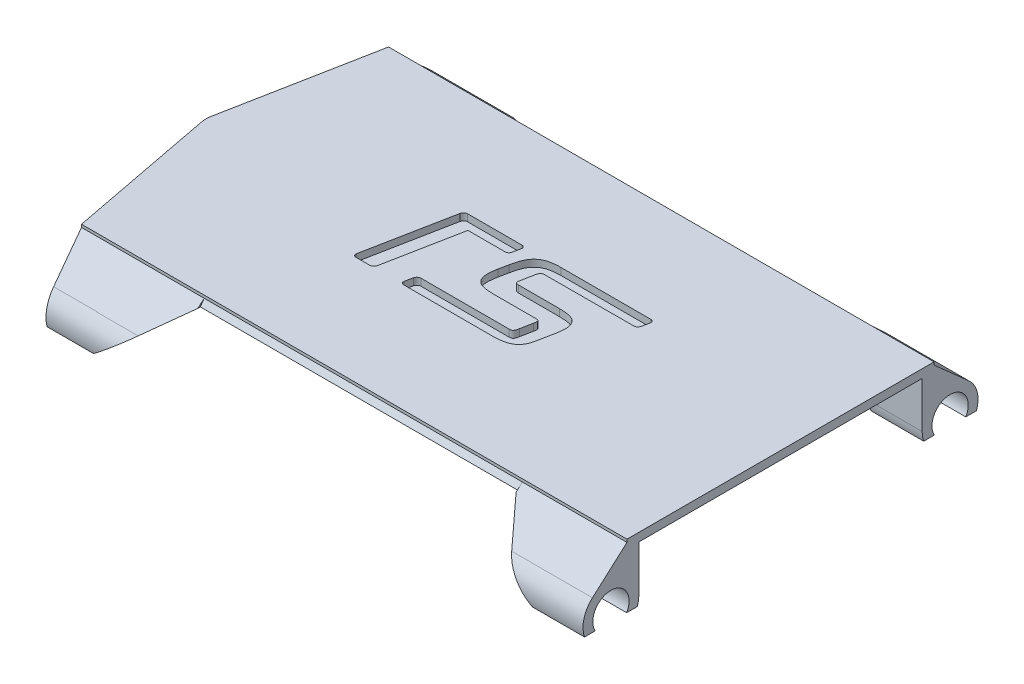
SolidWorks part; units mm, degrees
ref_plane "Front Plane" through (0, 0, 0) normal (0, 0, 1) x (1, 0, 0)
ref_plane "Top Plane" through (0, 0, 0) normal (0, 1, 0) x (1, 0, 0)
ref_plane "Right Plane" through (0, 0, 0) normal (1, 0, 0) x (0, 0, -1)
sketch "Sketch1" plane through (0, 0, 0) normal (0, 1, 0) x (1, 0, 0)
  line L0 (0, 0) -> (0, -110)
  line L1 (0, -110) -> (660, -110)
  line L2 (0, 0) -> (660, 0)
  line L3 (660, 0) -> (660, -110)
extrude "Boss-Extrude1" add sketch "Sketch1" along normal blind 2
sketch "Sketch4" plane through (0, 2, 0) normal (0, 1, 0) x (1, 0, 0)
  text T1 "CLAw" font "Republika II" height 50
extrude "Cut-Extrude1" cut sketch "Sketch4" against normal blind 37
sketch "Sketch6" plane through (0, 2, 0) normal (0, 1, 0) x (1, 0, 0)
  line L1 (348.7692, -11.8487) -> (398.7692, -11.8487)
  line L2 (348.7692, -11.8487) -> (348.7692, -61.8487)
  line L3 (348.7692, -61.8487) -> (398.7692, -61.8487)
  line L4 (398.7692, -11.8487) -> (398.7692, -61.8487)
  line L5 (348.7692, -11.8487) -> (398.7692, -61.8487) construction
  line L6 (348.7692, -61.8487) -> (398.7692, -11.8487) construction
  point P0 (373.7692, -36.8487)
extrude "Cut-Extrude3" cut sketch "Sketch6" against normal blind 37
fillet "Fillet2" radius 5 4 edges at (398.7692, 1, 11.8487) (398.7692, 1, 61.8487) (348.7692, 1, 61.8487) (348.7692, 1, 11.8487)
sketch "Sketch8" plane through (0, 0, 0) normal (-1, 0, 0) x (0, 0, 1)
  line L4 (0, 0) -> (110, 0)
  line L5 (110, 0) -> (110, 2)
  line L6 (110, 2) -> (0, 2)
  line L7 (0, 2) -> (0, 0)
  line L8 (0, 0) -> (110, 0)
  line L9 (110, 0) -> (110, 2)
  line L10 (110, 2) -> (0, 2)
  line L11 (0, 2) -> (0, 0)
  dimension "D1" = 0
extrude "Boss-Extrude3" add sketch "Sketch8" along normal blind 10
sketch "Sketch9" plane through (0, 2, 0) normal (0, 1, 0) x (1, 0, 0)
  line L0 (-10, -55) -> (22.7016, -110)
  line L1 (-10, -110) -> (-10, 0) construction
  line L2 (-10, -110) -> (660, -110) construction
  line L3 (22.7016, -110) -> (22.7016, 0)
  line L4 (660, 0) -> (-10, 0) construction
  line L5 (22.7016, 0) -> (-10, -55)
  line L6 (22.7016, 0) -> (-53.8685, 93.2317)
  line L7 (-53.8685, 93.2317) -> (-113.2593, -63.3442)
  line L8 (-113.2593, -63.3442) -> (-74.9743, -268.0218)
  line L9 (-74.9743, -268.0218) -> (22.7016, -110)
extrude "Cut-Extrude4" cut sketch "Sketch9" against normal blind 10 contours L8 L9 L0 L5 L6 L7 region at (-48.4537, 2, 78.706)
fillet "Fillet3" radius 5 3 edges at (22.7016, 1, 110) (22.7016, 1, 0) (-10, 1, 55)
sketch "Sketch10" plane through (0, 2, 0) normal (0, 1, 0) x (1, 0, 0)
  line L0 (348.7692, -36.8487) -> (398.7692, -36.8487)
  line L1 (348.7692, -16.8487) -> (348.7692, -56.8487) construction
  line L2 (398.7692, -56.8487) -> (398.7692, -16.8487) construction
  line L3 (398.7692, -36.8487) -> (373.7692, -36.8487)
  line L4 (373.7692, -36.8487) -> (373.7692, -11.8487)
  line L5 (393.7692, -11.8487) -> (353.7692, -11.8487) construction
  line L6 (351.2692, -14.3487) -> (396.2692, -14.3487)
  line L7 (351.2692, -14.3487) -> (351.2692, -59.3487)
  line L8 (396.2692, -14.3487) -> (396.2692, -59.3487)
  line L9 (351.2692, -59.3487) -> (396.2692, -59.3487)
  line L10 (351.2692, -14.3487) -> (396.2692, -59.3487) construction
  line L11 (396.2692, -14.3487) -> (351.2692, -59.3487) construction
  circle A0 centre (373.7692, -36.8487) radius 34.5365
extrude "Boss-Extrude4" add sketch "Sketch10" against normal up to surface (2 mm away) contours A0 L9 L7 L6 L8 region at (340.2096, 2, 36.8487) up to face at (373.7692, 0, 36.8487)
fillet "Fillet4" radius 5 4 edges at (351.2692, 1, 59.3487) (396.2692, 1, 59.3487) (396.2692, 1, 14.3487) (351.2692, 1, 14.3487)
sketch "Sketch11" plane through (0, 2, 0) normal (0, 1, 0) x (1, 0, 0)
  line L4 (351.2692, -19.3487) -> (351.2692, -54.3487)
  line L5 (-8.4807, -57.5553) -> (21.248, -107.5553)
  line L6 (25.5457, -110) -> (660, -110)
  line L7 (660, -110) -> (660, 0)
  line L8 (660, 0) -> (25.5457, 0)
  line L9 (21.248, -2.4447) -> (-8.4807, -52.4447)
  line L10 (-8.4807, -57.5553) -> (21.248, -107.5553)
  line L11 (25.5457, -110) -> (660, -110)
  line L12 (660, -110) -> (660, 0)
  line L13 (660, 0) -> (25.5457, 0)
  line L14 (21.248, -2.4447) -> (-8.4807, -52.4447)
  line L15 (391.2692, -14.3487) -> (356.2692, -14.3487)
  line L16 (396.2692, -54.3487) -> (396.2692, -19.3487)
  line L17 (356.2692, -59.3487) -> (391.2692, -59.3487)
  line L18 (351.2692, -19.3487) -> (351.2692, -54.3487)
  line L19 (391.2692, -14.3487) -> (356.2692, -14.3487)
  line L20 (396.2692, -54.3487) -> (396.2692, -19.3487)
  line L21 (356.2692, -59.3487) -> (391.2692, -59.3487)
  line L22 (145.7422, -85.0834) -> (159.989, -11.9696)
  line L23 (135.9807, -86.8724) -> (143.5902, -86.8724)
  line L24 (148.7886, -11.9696) -> (134.5418, -85.0834)
  line L25 (158.563, -9.7269) -> (150.9405, -9.7269)
  line L26 (93.4347, -76.1257) -> (99.0738, -47.4505)
  line L27 (124.884, -78.9906) -> (94.9514, -78.9906)
  line L28 (125.4155, -84.9927) -> (126.31, -80.8703)
  line L29 (92.981, -86.6909) -> (123.2636, -86.6909)
  line L30 (87.5104, -49.6025) -> (82.7658, -73.9737)
  line L31 (133.4788, -36.8724) -> (102.6646, -36.8724)
  line L32 (134.2047, -42.7837) -> (135.0084, -38.6613)
  line L33 (101.6794, -44.5856) -> (132.0528, -44.5856)
  line L34 (93.4347, -76.1257) -> (99.0738, -47.4505)
  line L35 (124.884, -78.9906) -> (94.9514, -78.9906)
  line L36 (125.4155, -84.9927) -> (126.31, -80.8703)
  line L37 (92.981, -86.6909) -> (123.2636, -86.6909)
  line L38 (87.5104, -49.6025) -> (82.7658, -73.9737)
  line L39 (133.4788, -36.8724) -> (102.6646, -36.8724)
  line L40 (134.2047, -42.7837) -> (135.0084, -38.6613)
  line L41 (101.6794, -44.5856) -> (132.0528, -44.5856)
  line L42 (145.7422, -85.0834) -> (159.989, -11.9696)
  line L43 (135.9807, -86.8724) -> (143.5902, -86.8724)
  line L44 (148.7886, -11.9696) -> (134.5418, -85.0834)
  line L45 (158.563, -9.7269) -> (150.9405, -9.7269)
  line L48 (201.7702, -47.4505) -> (197.7385, -67.9717)
  line L49 (164.1373, -44.5856) -> (200.2405, -44.5856)
  line L50 (172.1098, -63.2141) -> (186.7974, -63.2141)
  line L51 (167.5337, -76.2942) -> (169.5042, -66.079)
  line L52 (204.9073, -79.1721) -> (169.0634, -79.1721)
  line L53 (205.5296, -85.0834) -> (206.3333, -80.961)
  line L54 (167.093, -86.8724) -> (203.3776, -86.8724)
  line L55 (157.9537, -68.2309) -> (156.8778, -74.1423)
  line L56 (188.3271, -55.5138) -> (173.1858, -55.5138)
  line L57 (188.9493, -61.4251) -> (189.766, -57.3027)
  line L58 (172.1098, -63.2141) -> (186.7974, -63.2141)
  line L59 (167.5337, -76.2942) -> (169.5042, -66.079)
  line L60 (204.9073, -79.1721) -> (169.0634, -79.1721)
  line L61 (205.5296, -85.0834) -> (206.3333, -80.961)
  line L62 (167.093, -86.8724) -> (203.3776, -86.8724)
  line L63 (157.9537, -68.2309) -> (156.8778, -74.1423)
  line L64 (188.3271, -55.5138) -> (173.1858, -55.5138)
  line L65 (188.9493, -61.4251) -> (189.766, -57.3027)
  line L66 (163.5928, -38.6613) -> (162.6984, -42.7837)
  line L67 (202.1202, -36.8724) -> (165.654, -36.8724)
  line L68 (208.8482, -67.9717) -> (212.4261, -49.6025)
  line L69 (199.1645, -70.0329) -> (206.6963, -70.0329)
  line L70 (201.7702, -47.4505) -> (197.7385, -67.9717)
  line L71 (164.1373, -44.5856) -> (200.2405, -44.5856)
  line L72 (163.5928, -38.6613) -> (162.6984, -42.7837)
  line L73 (202.1202, -36.8724) -> (165.654, -36.8724)
  line L74 (208.8482, -67.9717) -> (212.4261, -49.6025)
  line L75 (199.1645, -70.0329) -> (206.6963, -70.0329)
  line L83 (229.7842, -36.8724) -> (221.9931, -36.8724)
  line L84 (237.6659, -74.0645) -> (231.3009, -38.1298)
  line L85 (254.6869, -38.1298) -> (237.6659, -74.0645)
  line L86 (266.1596, -36.8724) -> (256.5796, -36.8724)
  line L87 (270.282, -73.883) -> (267.6893, -38.1298)
  line L88 (289.7271, -38.0391) -> (270.282, -73.883)
  line L89 (296.2737, -36.7816) -> (291.6976, -36.7816)
  line L90 (272.5246, -85.6149) -> (297.5182, -39.115)
  line L91 (262.2187, -86.8724) -> (270.5542, -86.8724)
  line L92 (257.9148, -47.7098) -> (260.7798, -85.6149)
  line L93 (240.0901, -85.6149) -> (257.9148, -47.7098)
  line L94 (229.4212, -86.8724) -> (238.1197, -86.8724)
  line L95 (219.8412, -39.2058) -> (227.9952, -85.6149)
  line L96 (229.7842, -36.8724) -> (221.9931, -36.8724)
  line L97 (237.6659, -74.0645) -> (231.3009, -38.1298)
  line L98 (254.6869, -38.1298) -> (237.6659, -74.0645)
  line L99 (266.1596, -36.8724) -> (256.5796, -36.8724)
  line L100 (270.282, -73.883) -> (267.6893, -38.1298)
  line L101 (289.7271, -38.0391) -> (270.282, -73.883)
  line L102 (296.2737, -36.7816) -> (291.6976, -36.7816)
  line L103 (272.5246, -85.6149) -> (297.5182, -39.115)
  line L104 (262.2187, -86.8724) -> (270.5542, -86.8724)
  line L105 (257.9148, -47.7098) -> (260.7798, -85.6149)
  line L106 (240.0901, -85.6149) -> (257.9148, -47.7098)
  line L107 (229.4212, -86.8724) -> (238.1197, -86.8724)
  line L108 (219.8412, -39.2058) -> (227.9952, -85.6149)
  arc A3 (21.248, -107.5553) -> (25.5457, -110) centre (25.5457, -105) ccw
  arc A4 (25.5457, 0) -> (21.248, -2.4447) centre (25.5457, -5) ccw
  arc A5 (-8.4807, -52.4447) -> (-8.4807, -57.5553) centre (-4.183, -55) ccw
  arc A6 (21.248, -107.5553) -> (25.5457, -110) centre (25.5457, -105) ccw
  arc A7 (25.5457, 0) -> (21.248, -2.4447) centre (25.5457, -5) ccw
  arc A8 (-8.4807, -52.4447) -> (-8.4807, -57.5553) centre (-4.183, -55) ccw
  arc A10 (356.2692, -14.3487) -> (351.2692, -19.3487) centre (356.2692, -19.3487) ccw
  arc A11 (396.2692, -19.3487) -> (391.2692, -14.3487) centre (391.2692, -19.3487) ccw
  arc A12 (391.2692, -59.3487) -> (396.2692, -54.3487) centre (391.2692, -54.3487) ccw
  arc A13 (351.2692, -54.3487) -> (356.2692, -59.3487) centre (356.2692, -54.3487) ccw
  arc A14 (356.2692, -14.3487) -> (351.2692, -19.3487) centre (356.2692, -19.3487) ccw
  arc A15 (396.2692, -19.3487) -> (391.2692, -14.3487) centre (391.2692, -19.3487) ccw
  arc A16 (391.2692, -59.3487) -> (396.2692, -54.3487) centre (391.2692, -54.3487) ccw
  arc A17 (351.2692, -54.3487) -> (356.2692, -59.3487) centre (356.2692, -54.3487) ccw
  spline S4 degree 3 poles (5119.0165, 624.1049) (37.5916, -48.4897) (164.7722, -20.7291) (159.7895, -10.5967) (159.5096, -10.1557) (159.2245, -9.9114) (152.3179, -6.6242) (125.7503, -85.5656) (1307.2548, 4856.2883) knots -10.252536 -10.252536 -10.252536 -10.252536 0.247453 0.514127 0.651326 0.771326 0.885869 8.19178 8.19178 8.19178 8.19178 only from (159.989, -11.9696) to (158.563, -9.7269)
  spline S5 degree 3 poles (1746.4382, -4822.5753) (85.6374, 18.1841) (135.4862, -92.9254) (144.9608, -86.3561) (153.405, -77.5738) (59.1372, -8.4502) (4467.9591, -2597.936) knots -10.519124 -10.519124 -10.519124 -10.519124 0.238341 0.493659 0.754958 12.251469 12.251469 12.251469 12.251469 only from (143.5902, -86.8724) to (145.7422, -85.0834)
  spline S6 degree 3 poles (-4813.8307, -799.2887) (260.4989, -48.4881) (129.764, -77.4859) (134.7831, -86.3687) (142.7775, -92.9818) (196.8871, 22.0279) (-1618.5468, -4768.53) knots -10.241358 -10.241358 -10.241358 -10.241358 0.254875 0.502398 0.750259 11.547922 11.547922 11.547922 11.547922 only from (134.5418, -85.0834) to (135.9807, -86.8724)
  spline S7 degree 3 poles (-2018.1341, 4494.7129) (222.871, -112.249) (157.5447, -2.3836) (149.5656, -10.4872) (140.9905, -22.4408) (223.9073, -83.9812) (-4259.7114, 2346.2278) knots -9.215893 -9.215893 -9.215893 -9.215893 0.217741 0.484007 0.757024 13.664578 13.664578 13.664578 13.664578 only from (150.9405, -9.7269) to (148.7886, -11.9696)
  spline S8 degree 3 poles (-4821.5246, 836.4901) (148.5767, -103.6282) (92.8249, -68.8611) (99.4434, -46.0062) (99.6685, -45.4993) (99.9, -45.1098) (100.2334, -44.8621) (100.6318, -44.6913) (115.464, -42.282) (133.016, -110.7737) (-56.6754, 4952.4083) knots -15.767879 -15.767879 -15.767879 -15.767879 0.191655 0.352665 0.475864 0.571897 0.65833 0.75509 0.866531 10.878226 10.878226 10.878226 10.878226 only from (99.0738, -47.4505) to (101.6794, -44.5856)
  spline S9 degree 3 poles (169.7585, -5078.1775) (123.2755, -14.6975) (108.8907, -81.2253) (93.9516, -78.8921) (93.6054, -78.7167) (93.3481, -78.4608) (93.2407, -78.0636) (93.2324, -77.5513) (94.7269, -58.7427) (175.6167, -52.6142) (-4836.4429, 755.7208) knots -10.63996 -10.63996 -10.63996 -10.63996 0.13985 0.253034 0.342388 0.420899 0.511149 0.634982 0.797202 14.318099 14.318099 14.318099 14.318099 only from (94.9514, -78.9906) to (93.4347, -76.1257)
  spline S10 degree 3 poles (5105.7769, 370.3031) (-0.7231, -112.5931) (130.6654, -89.5963) (126.1292, -79.5053) (118.073, -72.5768) (62.794, -196.3962) (1804.2586, 4630.0286) knots -10.793484 -10.793484 -10.793484 -10.793484 0.268474 0.504404 0.741689 11.2333 11.2333 11.2333 11.2333 only from (126.31, -80.8703) to (124.884, -78.9906)
  spline S11 degree 3 poles (1613.3455, -4859.2502) (68.5222, 13.8167) (114.4009, -92.4132) (124.6312, -86.2195) (133.0883, -78.0184) (36.7322, -6.9644) (4424.5015, -2637.4299) knots -11.262406 -11.262406 -11.262406 -11.262406 0.243251 0.49708 0.753982 12.024347 12.024347 12.024347 12.024347 only from (123.2636, -86.6909) to (125.4155, -84.9927)
  spline S12 degree 3 poles (-4826.4304, 866.5979) (170.3812, -8.9265) (87.3715, -36.3481) (82.2604, -77.2706) (82.1824, -78.7215) (82.1924, -80.0197) (82.3476, -81.1875) (82.6294, -82.2261) (83.0332, -83.1603) (83.5844, -83.9717) (84.2753, -84.678) (85.111, -85.256) (86.0833, -85.7282) (87.1894, -86.1022) (88.44, -86.3617) (89.8257, -86.5563) (127.5802, -89.3822) (167.4988, -10.8224) (40.5827, -5084.9902) knots -5.826315 -5.826315 -5.826315 -5.826315 0.087079 0.166501 0.237186 0.300785 0.357259 0.410017 0.458698 0.506315 0.553528 0.603277 0.655033 0.71214 0.774627 0.842701 0.917951 6.34104 6.34104 6.34104 6.34104 only from (82.7658, -73.9737) to (92.981, -86.6909)
  spline S13 degree 3 poles (89.6027, 4961.592) (179.9003, -109.8247) (138.9176, -34.2589) (99.4352, -37.0043) (97.9783, -37.2185) (96.6317, -37.482) (95.3921, -37.8429) (94.2494, -38.3097) (93.2086, -38.8989) (92.25, -39.5883) (91.3935, -40.3995) (90.6162, -41.3193) (89.933, -42.3633) (89.3191, -43.5257) (88.7891, -44.8274) (88.3134, -46.2761) (77.7385, -84.5816) (149.0281, -141.6441) (-4802.8385, 984.6515) knots -5.117713 -5.117713 -5.117713 -5.117713 0.075754 0.147021 0.212931 0.27417 0.331868 0.386719 0.440192 0.492746 0.5455 0.598833 0.654739 0.713373 0.775798 0.843961 0.918866 6.129901 6.129901 6.129901 6.129901 only from (102.6646, -36.8724) to (87.5104, -49.6025)
  spline S14 degree 3 poles (5043.8317, 910.2798) (7.2427, -81.3695) (140.1753, -45.7434) (134.7154, -37.3852) (126.6273, -30.6359) (70.258, -147.5052) (1933.8052, 4627.334) knots -9.783819 -9.783819 -9.783819 -9.783819 0.249602 0.492469 0.745872 11.540394 11.540394 11.540394 11.540394 only from (135.0084, -38.6613) to (133.4788, -36.8724)
  spline S15 degree 3 poles (1704.4134, -4790.4582) (75.4545, 58.8418) (123.9048, -50.5857) (133.416, -44.0697) (141.982, -34.7264) (51.7381, 32.2842) (4464.2433, -2542.2459) knots -10.493827 -10.493827 -10.493827 -10.493827 0.233907 0.489043 0.753411 12.753303 12.753303 12.753303 12.753303 only from (132.0528, -44.5856) to (134.2047, -42.7837)
  spline S16 degree 3 poles (99.0738, -47.4505) (99.1357, -47.1777) (99.2495, -46.6757) (99.4434, -46.0062) (99.6685, -45.4993) (99.9, -45.1098) (100.2334, -44.8621) (100.6318, -44.6913) (101.1277, -44.6107) (101.4848, -44.5945) (101.6794, -44.5856) knots 0 0 0 0 0.191655 0.352665 0.475864 0.571897 0.65833 0.75509 0.866531 1 1 1 1
  spline S17 degree 3 poles (94.9514, -78.9906) (94.7613, -78.9814) (94.4173, -78.9648) (93.9516, -78.8921) (93.6054, -78.7167) (93.3481, -78.4608) (93.2407, -78.0636) (93.2324, -77.5513) (93.2853, -76.8853) (93.3813, -76.397) (93.4347, -76.1257) knots 0 0 0 0 0.13985 0.253034 0.342388 0.420899 0.511149 0.634982 0.797202 1 1 1 1
  spline S18 degree 3 poles (126.31, -80.8703) (126.3485, -80.6215) (126.4209, -80.1541) (126.1292, -79.5053) (125.5917, -79.0431) (125.1265, -79.0086) (124.884, -78.9906) knots 0 0 0 0 0.268474 0.504404 0.741689 1 1 1 1
  spline S19 degree 3 poles (123.2636, -86.6909) (123.502, -86.6637) (123.9893, -86.6081) (124.6312, -86.2195) (125.1744, -85.6927) (125.3363, -85.2226) (125.4155, -84.9927) knots 0 0 0 0 0.243251 0.49708 0.753982 1 1 1 1
  spline S20 degree 3 poles (82.7658, -73.9737) (82.6609, -74.5562) (82.4604, -75.6698) (82.2604, -77.2706) (82.1824, -78.7215) (82.1924, -80.0197) (82.3476, -81.1875) (82.6294, -82.2261) (83.0332, -83.1603) (83.5844, -83.9717) (84.2753, -84.678) (85.111, -85.256) (86.0833, -85.7282) (87.1894, -86.1022) (88.44, -86.3617) (89.8257, -86.5563) (91.3543, -86.6707) (92.4233, -86.6839) (92.981, -86.6909) knots 0 0 0 0 0.087079 0.166501 0.237186 0.300785 0.357259 0.410017 0.458698 0.506315 0.553528 0.603277 0.655033 0.71214 0.774627 0.842701 0.917951 1 1 1 1
  spline S21 degree 3 poles (102.6646, -36.8724) (102.1028, -36.8799) (101.0123, -36.8946) (99.4352, -37.0043) (97.9783, -37.2185) (96.6317, -37.482) (95.3921, -37.8429) (94.2494, -38.3097) (93.2086, -38.8989) (92.25, -39.5883) (91.3935, -40.3995) (90.6162, -41.3193) (89.933, -42.3633) (89.3191, -43.5257) (88.7891, -44.8274) (88.3134, -46.2761) (87.8706, -47.8801) (87.6336, -49.0133) (87.5104, -49.6025) knots 0 0 0 0 0.075754 0.147021 0.212931 0.27417 0.331868 0.386719 0.440192 0.492746 0.5455 0.598833 0.654739 0.713373 0.775798 0.843961 0.918866 1 1 1 1
  spline S22 degree 3 poles (135.0084, -38.6613) (135.0399, -38.4312) (135.1021, -37.9772) (134.7154, -37.3852) (134.1778, -36.9366) (133.712, -36.8938) (133.4788, -36.8724) knots 0 0 0 0 0.249602 0.492469 0.745872 1 1 1 1
  spline S23 degree 3 poles (132.0528, -44.5856) (132.2877, -44.5599) (132.7789, -44.5062) (133.416, -44.0697) (133.9402, -43.4979) (134.1186, -43.0162) (134.2047, -42.7837) knots 0 0 0 0 0.233907 0.489043 0.753411 1 1 1 1
  spline S24 degree 3 poles (159.989, -11.9696) (160.0209, -11.7202) (160.0872, -11.2019) (159.7895, -10.5967) (159.5096, -10.1557) (159.2245, -9.9114) (158.9052, -9.7594) (158.6769, -9.7377) (158.563, -9.7269) knots 0 0 0 0 0.247453 0.514127 0.651326 0.771326 0.885869 1 1 1 1
  spline S25 degree 3 poles (143.5902, -86.8724) (143.8299, -86.8475) (144.3263, -86.796) (144.9608, -86.3561) (145.4962, -85.7993) (145.6619, -85.3169) (145.7422, -85.0834) knots 0 0 0 0 0.238341 0.493659 0.754958 1 1 1 1
  spline S26 degree 3 poles (134.5418, -85.0834) (134.5077, -85.3119) (134.4405, -85.7623) (134.7831, -86.3687) (135.3105, -86.805) (135.7568, -86.8499) (135.9807, -86.8724) knots 0 0 0 0 0.254875 0.502398 0.750259 1 1 1 1
  spline S27 degree 3 poles (150.9405, -9.7269) (150.7018, -9.772) (150.1712, -9.8721) (149.5656, -10.4872) (149.0667, -11.1826) (148.8776, -11.7176) (148.7886, -11.9696) knots 0 0 0 0 0.217741 0.484007 0.757024 1 1 1 1
  spline S30 degree 3 poles (-4762.4185, -694.8614) (316.3853, -32.6452) (193.3206, -59.3419) (197.9606, -69.3721) (204.8576, -76.997) (271.8684, 38.3013) (-1981.3407, -4569.0835) knots -10.549817 -10.549817 -10.549817 -10.549817 0.246801 0.508891 0.764045 10.553224 10.553224 10.553224 10.553224 only from (197.7385, -67.9717) to (199.1645, -70.0329)
  spline S31 degree 3 poles (125.6448, 4954.4444) (171.9139, -108.8774) (186.3014, -42.3509) (201.2403, -44.6841) (201.5865, -44.8595) (201.8437, -45.1154) (201.9501, -45.5083) (201.9599, -46.0206) (200.2839, -66.2648) (125.5232, -74.9625) (5132.3522, -874.6847) knots -10.645446 -10.645446 -10.645446 -10.645446 0.139924 0.253168 0.342568 0.421121 0.511418 0.632148 0.797617 15.387682 15.387682 15.387682 15.387682 only from (200.2405, -44.5856) to (201.7702, -47.4505)
  spline S32 degree 3 poles (1789.6453, -4798.917) (128.8445, 41.8424) (178.6934, -69.2671) (188.168, -62.6978) (196.6121, -53.9156) (102.3443, 15.208) (4511.1663, -2574.2777) knots -10.519124 -10.519124 -10.519124 -10.519124 0.238341 0.493659 0.754958 12.251469 12.251469 12.251469 12.251469 only from (186.7974, -63.2141) to (188.9493, -61.4251)
  spline S33 degree 3 poles (-4737.0146, 892.8675) (223.3481, -121.2444) (163.4442, -86.1054) (169.8763, -64.644) (170.0989, -64.141) (170.33, -63.7502) (170.6668, -63.5059) (171.0584, -63.3156) (186.6212, -60.9841) (200.8281, -126.3612) (306.7252, 4934.426) knots -14.845291 -14.845291 -14.845291 -14.845291 0.191965 0.350404 0.473801 0.569989 0.656562 0.754694 0.866315 11.339935 11.339935 11.339935 11.339935 only from (169.5042, -66.079) to (172.1098, -63.2141)
  spline S34 degree 3 poles (243.9291, -5078.0856) (197.3861, -14.8812) (183.0024, -81.4067) (168.0636, -79.0735) (167.7174, -78.8981) (167.4601, -78.6423) (167.3527, -78.2451) (167.3442, -77.7284) (168.9891, -57.5787) (244.1387, -48.8308) (-4765.3731, 736.5916) knots -10.611726 -10.611726 -10.611726 -10.611726 0.139482 0.252368 0.341486 0.419791 0.509803 0.63331 0.798256 15.270455 15.270455 15.270455 15.270455 only from (169.0634, -79.1721) to (167.5337, -76.2942)
  spline S35 degree 3 poles (5136.6795, 748.2893) (78.7046, -120.529) (211.2178, -88.2739) (206.0839, -79.6924) (198.6305, -72.9) (139.7098, -190.3795) (2100.6058, 4547.1099) knots -10.123556 -10.123556 -10.123556 -10.123556 0.256189 0.500613 0.748972 11.281667 11.281667 11.281667 11.281667 only from (206.3333, -80.961) to (204.9073, -79.1721)
  spline S36 degree 3 poles (1800.9134, -4824.4512) (146.1601, 16.712) (195.2921, -92.885) (204.7361, -86.3565) (213.3053, -77.3439) (121.5187, -8.3329) (4508.7142, -2630.5463) knots -10.496031 -10.496031 -10.496031 -10.496031 0.234671 0.490641 0.752605 12.552539 12.552539 12.552539 12.552539 only from (203.3776, -86.8724) to (205.5296, -85.0834)
  spline S37 degree 3 poles (-4751.9198, 867.8636) (243.9443, -7.7018) (161.5816, -35.8922) (156.3723, -77.4521) (156.2945, -78.903) (156.3044, -80.2012) (156.4597, -81.3689) (156.7414, -82.4076) (157.1453, -83.3416) (157.696, -84.1538) (158.3864, -84.8545) (159.2138, -85.4456) (160.1899, -85.9025) (161.2914, -86.2871) (162.5435, -86.5437) (163.9334, -86.7369) (201.5814, -89.5728) (241.387, -10.7572) (115.0296, -5085.2901) knots -5.916393 -5.916393 -5.916393 -5.916393 0.087644 0.16701 0.237645 0.301199 0.357633 0.410354 0.459 0.506584 0.553764 0.602958 0.655248 0.711715 0.774157 0.842812 0.918009 6.320997 6.320997 6.320997 6.320997 only from (156.8778, -74.1423) to (167.093, -86.8724)
  spline S38 degree 3 poles (160.1506, 4942.9246) (250.421, -128.4657) (209.4387, -52.9003) (169.9563, -55.6457) (168.4994, -55.8599) (167.1529, -56.1234) (165.9132, -56.4843) (164.7705, -56.9511) (163.7298, -57.5405) (162.7706, -58.2292) (161.9146, -59.0448) (161.1243, -59.9597) (160.4275, -61.0039) (159.8039, -62.1695) (159.242, -63.465) (158.7547, -64.9156) (148.0433, -104.0672) (216.714, -161.3651) (-4733.0477, 962.0102) knots -5.112354 -5.112354 -5.112354 -5.112354 0.075675 0.146867 0.212708 0.273883 0.331521 0.386315 0.439731 0.49223 0.544929 0.598583 0.654753 0.713601 0.776414 0.844692 0.919519 6.239873 6.239873 6.239873 6.239873 only from (173.1858, -55.5138) to (157.9537, -68.2309)
  spline S39 degree 3 poles (5112.4364, 816.3394) (64.5764, -97.9419) (194.6461, -64.7285) (189.5045, -56.0342) (182.0324, -49.2389) (123.4683, -166.8138) (2070.8164, 4576.2565) knots -10.270456 -10.270456 -10.270456 -10.270456 0.256083 0.500542 0.748936 11.28685 11.28685 11.28685 11.28685 only from (189.766, -57.3027) to (188.3271, -55.5138)
  spline S40 degree 3 poles (186.7974, -63.2141) (187.0371, -63.1892) (187.5335, -63.1377) (188.168, -62.6978) (188.7033, -62.141) (188.8691, -61.6586) (188.9493, -61.4251) knots 0 0 0 0 0.238341 0.493659 0.754958 1 1 1 1
  spline S41 degree 3 poles (169.5042, -66.079) (169.5655, -65.806) (169.6773, -65.3078) (169.8763, -64.644) (170.0989, -64.141) (170.33, -63.7502) (170.6668, -63.5059) (171.0584, -63.3156) (171.5587, -63.2406) (171.9154, -63.2234) (172.1098, -63.2141) knots 0 0 0 0 0.191965 0.350404 0.473801 0.569989 0.656562 0.754694 0.866315 1 1 1 1
  spline S42 degree 3 poles (169.0634, -79.1721) (168.8733, -79.1629) (168.5293, -79.1463) (168.0636, -79.0735) (167.7174, -78.8981) (167.4601, -78.6423) (167.3527, -78.2451) (167.3442, -77.7284) (167.3988, -77.0592) (167.4858, -76.5657) (167.5337, -76.2942) knots 0 0 0 0 0.139482 0.252368 0.341486 0.419791 0.509803 0.63331 0.798256 1 1 1 1
  spline S43 degree 3 poles (206.3333, -80.961) (206.3686, -80.7317) (206.4376, -80.2836) (206.0839, -79.6924) (205.5811, -79.2342) (205.1327, -79.1929) (204.9073, -79.1721) knots 0 0 0 0 0.256189 0.500613 0.748972 1 1 1 1
  spline S44 degree 3 poles (203.3776, -86.8724) (203.6127, -86.8468) (204.1042, -86.7933) (204.7361, -86.3565) (205.2685, -85.7966) (205.4442, -85.3165) (205.5296, -85.0834) knots 0 0 0 0 0.234671 0.490641 0.752605 1 1 1 1
  spline S45 degree 3 poles (156.8778, -74.1423) (156.773, -74.729) (156.5735, -75.8472) (156.3723, -77.4521) (156.2945, -78.903) (156.3044, -80.2012) (156.4597, -81.3689) (156.7414, -82.4076) (157.1453, -83.3416) (157.696, -84.1538) (158.3864, -84.8545) (159.2138, -85.4456) (160.1899, -85.9025) (161.2914, -86.2871) (162.5435, -86.5437) (163.9334, -86.7369) (165.4663, -86.8523) (166.5353, -86.8655) (167.093, -86.8724) knots 0 0 0 0 0.087644 0.16701 0.237645 0.301199 0.357633 0.410354 0.459 0.506584 0.553764 0.602958 0.655248 0.711715 0.774157 0.842812 0.918009 1 1 1 1
  spline S46 degree 3 poles (173.1858, -55.5138) (172.6239, -55.5214) (171.5334, -55.536) (169.9563, -55.6457) (168.4994, -55.8599) (167.1529, -56.1234) (165.9132, -56.4843) (164.7705, -56.9511) (163.7298, -57.5405) (162.7706, -58.2292) (161.9146, -59.0448) (161.1243, -59.9597) (160.4275, -61.0039) (159.8039, -62.1695) (159.242, -63.465) (158.7547, -64.9156) (158.3163, -66.5178) (158.0775, -67.6462) (157.9537, -68.2309) knots 0 0 0 0 0.075675 0.146867 0.212708 0.273883 0.331521 0.386315 0.439731 0.49223 0.544929 0.598583 0.654753 0.713601 0.776414 0.844692 0.919519 1 1 1 1
  spline S47 degree 3 poles (189.766, -57.3027) (189.7958, -57.0734) (189.854, -56.6251) (189.5045, -56.0342) (189.0006, -55.5759) (188.5524, -55.5346) (188.3271, -55.5138) knots 0 0 0 0 0.256083 0.500542 0.748936 1 1 1 1
  spline S48 degree 3 poles (-4803.0766, -624.2829) (285.6346, -9.4495) (158.1638, -34.7685) (162.9198, -44.0832) (171.1115, -50.7249) (223.6463, 65.8818) (-1510.0259, -4755.7117) knots -10.454716 -10.454716 -10.454716 -10.454716 0.253098 0.501097 0.74723 11.599317 11.599317 11.599317 11.599317 only from (162.6984, -42.7837) to (164.1373, -44.5856)
  spline S49 degree 3 poles (-1519.4317, 4670.2452) (224.9322, -142.5009) (173.1695, -30.728) (164.3401, -37.4) (156.0718, -46.5998) (248.0329, -113.954) (-4172.5389, 2450.0963) knots -10.294502 -10.294502 -10.294502 -10.294502 0.235772 0.492631 0.748602 12.818541 12.818541 12.818541 12.818541 only from (165.654, -36.8724) to (163.5928, -38.6613)
  spline S50 degree 3 poles (5109.1622, -1048.7438) (121.3107, -135.7429) (206.1446, -97.6264) (213.0642, -45.482) (213.1556, -43.7743) (213.1324, -42.3154) (212.9601, -41.0739) (212.6337, -40.0205) (212.1893, -39.1201) (211.5517, -38.4181) (210.8012, -37.8638) (209.9164, -37.4601) (208.9115, -37.1752) (207.7758, -37.0361) (206.5281, -36.9758) (205.1631, -36.8986) (85.151, -35.764) (-31.2951, -56.8865) (-835.2796, 4842.5293) knots -7.105488 -7.105488 -7.105488 -7.105488 0.106501 0.199505 0.279761 0.346572 0.404273 0.45516 0.501055 0.544064 0.587051 0.631323 0.679943 0.733265 0.791665 0.855487 0.925319 17.651409 17.651409 17.651409 17.651409 only from (212.4261, -49.6025) to (202.1202, -36.8724)
  spline S51 degree 3 poles (2195.1702, -4657.396) (139.2752, 34.5314) (199.7326, -76.9319) (208.0602, -69.3612) (216.6468, -58.6365) (132.0961, 5.2833) (4562.879, -2525.2636) knots -9.559211 -9.559211 -9.559211 -9.559211 0.224501 0.485371 0.758537 13.24189 13.24189 13.24189 13.24189 only from (206.6963, -70.0329) to (208.8482, -67.9717)
  spline S52 degree 3 poles (197.7385, -67.9717) (197.7087, -68.2078) (197.6472, -68.6947) (197.9606, -69.3721) (198.4646, -69.9293) (198.9374, -69.9993) (199.1645, -70.0329) knots 0 0 0 0 0.246801 0.508891 0.764045 1 1 1 1
  spline S53 degree 3 poles (200.2405, -44.5856) (200.4306, -44.5948) (200.7746, -44.6114) (201.2403, -44.6841) (201.5865, -44.8595) (201.8437, -45.1154) (201.9501, -45.5083) (201.9599, -46.0206) (201.9048, -46.6855) (201.818, -47.179) (201.7702, -47.4505) knots 0 0 0 0 0.139924 0.253168 0.342568 0.421121 0.511418 0.632148 0.797617 1 1 1 1
  spline S54 degree 3 poles (162.6984, -42.7837) (162.6662, -43.0113) (162.6026, -43.4619) (162.9198, -44.0832) (163.4591, -44.5204) (163.9092, -44.5637) (164.1373, -44.5856) knots 0 0 0 0 0.253098 0.501097 0.74723 1 1 1 1
  spline S55 degree 3 poles (165.654, -36.8724) (165.4224, -36.8967) (164.9386, -36.9477) (164.3401, -37.4) (163.8379, -37.9587) (163.674, -38.4285) (163.5928, -38.6613) knots 0 0 0 0 0.235772 0.492631 0.748602 1 1 1 1
  spline S56 degree 3 poles (212.4261, -49.6025) (212.557, -48.8559) (212.8021, -47.4573) (213.0642, -45.482) (213.1556, -43.7743) (213.1324, -42.3154) (212.9601, -41.0739) (212.6337, -40.0205) (212.1893, -39.1201) (211.5517, -38.4181) (210.8012, -37.8638) (209.9164, -37.4601) (208.9115, -37.1752) (207.7758, -37.0361) (206.5281, -36.9758) (205.1631, -36.8986) (203.6801, -36.8846) (202.6517, -36.8765) (202.1202, -36.8724) knots 0 0 0 0 0.106501 0.199505 0.279761 0.346572 0.404273 0.45516 0.501055 0.544064 0.587051 0.631323 0.679943 0.733265 0.791665 0.855487 0.925319 1 1 1 1
  spline S57 degree 3 poles (206.6963, -70.0329) (206.934, -69.9965) (207.448, -69.9178) (208.0602, -69.3612) (208.5718, -68.7223) (208.7599, -68.2114) (208.8482, -67.9717) knots 0 0 0 0 0.224501 0.485371 0.758537 1 1 1 1
  spline S62 degree 3 poles (-1320.8955, 4718.7982) (286.4211, -156.1406) (231.1867, -29.6394) (220.4252, -37.4235) (220.0292, -37.8784) (219.8689, -38.2947) (217.9244, -47.5265) (312.7886, -58.8001) (-4779.1954, 47.2158) knots -9.933686 -9.933686 -9.933686 -9.933686 0.254097 0.50354 0.627839 0.74781 0.867516 8.328057 8.328057 8.328057 8.328057 only from (221.9931, -36.8724) to (219.8412, -39.2058)
  spline S63 degree 3 poles (4597.1874, 2398.5692) (152.5188, -101.0679) (237.0237, -43.6542) (230.7795, -37.2613) (223.2229, -31.8319) (176.8624, -131.7987) (1940.9983, 4660.8525) knots -11.693366 -11.693366 -11.693366 -11.693366 0.224095 0.485868 0.748868 13.164481 13.164481 13.164481 13.164481 only from (231.3009, -38.1298) to (229.7842, -36.8724)
  spline S64 degree 3 poles (-1113.0004, 4771.5993) (302.8663, -126.0447) (264.882, -32.2485) (255.4456, -37.2194) (247.3887, -43.245) (327.5097, -118.682) (-3685.0495, 3040.1344) knots -12.443679 -12.443679 -12.443679 -12.443679 0.236131 0.500383 0.76201 12.559139 12.559139 12.559139 12.559139 only from (256.5796, -36.8724) to (254.6869, -38.1298)
  spline S65 degree 3 poles (4602.9245, 2452.0735) (192.1407, -101.3164) (273.5229, -43.8969) (267.156, -37.2609) (259.5676, -31.8334) (213.7095, -131.8208) (1956.0923, 4668.6581) knots -12.071933 -12.071933 -12.071933 -12.071933 0.225854 0.487033 0.749437 13.153541 13.153541 13.153541 13.153541 only from (267.6893, -38.1298) to (266.1596, -36.8724)
  spline S66 degree 3 poles (-1027.3685, 4785.7403) (336.7841, -121.9279) (300.5217, -32.2496) (290.5295, -37.1246) (282.2381, -42.9722) (361.428, -120.5959) (-3586.6884, 3119.4806) knots -12.690287 -12.690287 -12.690287 -12.690287 0.230164 0.502129 0.765332 12.320158 12.320158 12.320158 12.320158 only from (291.6976, -36.7816) to (289.7271, -38.0391)
  spline S67 degree 3 poles (5082.9039, -1487.4386) (207.411, -33.0123) (296.3071, -48.6308) (297.7764, -38.2185) (297.7614, -37.8114) (297.6238, -37.4486) (297.4067, -37.148) (297.0987, -36.9263) (287.9951, -33.8735) (266.93, -119.3728) (945.1759, 4920.4356) knots -9.078418 -9.078418 -9.078418 -9.078418 0.155503 0.2867 0.408808 0.521985 0.634408 0.741337 0.861918 9.22575 9.22575 9.22575 9.22575 only from (297.5182, -39.115) to (296.2737, -36.7816)
  spline S68 degree 3 poles (1504.1944, -4931.9312) (227.5393, -1.9101) (261.7997, -91.3186) (271.6892, -86.5372) (280.7448, -79.4285) (212.4556, -6.3062) (4089.446, -3314.7179) knots -12.569583 -12.569583 -12.569583 -12.569583 0.226516 0.483636 0.752012 14.184086 14.184086 14.184086 14.184086 only from (270.5542, -86.8724) to (272.5246, -85.6149)
  spline S69 degree 3 poles (-4301.2842, -2130.9366) (349.6497, -29.0604) (255.5493, -80.3118) (261.228, -86.4949) (269.0611, -91.7861) (312.9485, 3.8543) (-1402.9978, -4801.0159) knots -10.966111 -10.966111 -10.966111 -10.966111 0.220121 0.47817 0.750832 13.623349 13.623349 13.623349 13.623349 only from (260.7798, -85.6149) to (262.2187, -86.8724)
  spline S70 degree 3 poles (1471.7599, -4931.9312) (195.1048, -1.9101) (229.3652, -91.3186) (239.2546, -86.5372) (248.3103, -79.4285) (180.021, -6.3062) (4057.0115, -3314.7179) knots -12.569583 -12.569583 -12.569583 -12.569583 0.226516 0.483636 0.752012 14.184086 14.184086 14.184086 14.184086 only from (238.1197, -86.8724) to (240.0901, -85.6149)
  spline S71 degree 3 poles (-4368.6489, -2052.2108) (315.6585, -31.1581) (222.8645, -80.0348) (228.4295, -86.4991) (236.3834, -91.7672) (278.7893, 3.5883) (-1373.1022, -4822.7076) knots -11.226242 -11.226242 -11.226242 -11.226242 0.220983 0.476127 0.749857 13.762527 13.762527 13.762527 13.762527 only from (227.9952, -85.6149) to (229.4212, -86.8724)
  spline S72 degree 3 poles (221.9931, -36.8724) (221.6818, -36.902) (221.065, -36.9608) (220.4252, -37.4235) (220.0292, -37.8784) (219.8689, -38.2947) (219.775, -38.7409) (219.8184, -39.0457) (219.8412, -39.2058) knots 0 0 0 0 0.254097 0.50354 0.627839 0.74781 0.867516 1 1 1 1
  spline S73 degree 3 poles (231.3009, -38.1298) (231.2549, -37.9771) (231.1553, -37.6461) (230.7795, -37.2613) (230.3264, -36.9357) (229.9621, -36.8932) (229.7842, -36.8724) knots 0 0 0 0 0.224095 0.485868 0.748868 1 1 1 1
  spline S74 degree 3 poles (256.5796, -36.8724) (256.3906, -36.8917) (255.9901, -36.9326) (255.4456, -37.2194) (254.9462, -37.5929) (254.7706, -37.9566) (254.6869, -38.1298) knots 0 0 0 0 0.236131 0.500383 0.76201 1 1 1 1
  spline S75 degree 3 poles (267.6893, -38.1298) (267.6382, -37.9774) (267.5281, -37.6488) (267.156, -37.2609) (266.7016, -36.9358) (266.3374, -36.8932) (266.1596, -36.8724) knots 0 0 0 0 0.225854 0.487033 0.749437 1 1 1 1
  spline S76 degree 3 poles (291.6976, -36.7816) (291.5091, -36.8023) (291.0979, -36.8474) (290.5295, -37.1246) (290.0016, -37.497) (289.815, -37.8654) (289.7271, -38.0391) knots 0 0 0 0 0.230164 0.502129 0.765332 1 1 1 1
  spline S77 degree 3 poles (297.5182, -39.115) (297.5867, -38.9575) (297.713, -38.6671) (297.7764, -38.2185) (297.7614, -37.8114) (297.6238, -37.4486) (297.4067, -37.148) (297.0987, -36.9263) (296.7113, -36.7964) (296.426, -36.7868) (296.2737, -36.7816) knots 0 0 0 0 0.155503 0.2867 0.408808 0.521985 0.634408 0.741337 0.861918 1 1 1 1
  spline S78 degree 3 poles (270.5542, -86.8724) (270.7382, -86.8516) (271.1309, -86.8071) (271.6892, -86.5372) (272.191, -86.1433) (272.4164, -85.7863) (272.5246, -85.6149) knots 0 0 0 0 0.226516 0.483636 0.752012 1 1 1 1
  spline S79 degree 3 poles (260.7798, -85.6149) (260.8064, -85.7674) (260.8642, -86.0987) (261.228, -86.4949) (261.6838, -86.8028) (262.0458, -86.8499) (262.2187, -86.8724) knots 0 0 0 0 0.220121 0.47817 0.750832 1 1 1 1
  spline S80 degree 3 poles (238.1197, -86.8724) (238.3036, -86.8516) (238.6964, -86.8071) (239.2546, -86.5372) (239.7565, -86.1433) (239.9819, -85.7863) (240.0901, -85.6149) knots 0 0 0 0 0.226516 0.483636 0.752012 1 1 1 1
  spline S81 degree 3 poles (227.9952, -85.6149) (228.0224, -85.7669) (228.0811, -86.0943) (228.4295, -86.4991) (228.8871, -86.8021) (229.2486, -86.8497) (229.4212, -86.8724) knots 0 0 0 0 0.220983 0.476127 0.749857 1 1 1 1
  dimension "D1" = 0
  dimension "D2" = 0
  dimension "D3" = 0
  dimension "D4" = 0
  dimension "D5" = 0
  dimension "D6" = 0
  dimension "D7" = 0
extrude "Boss-Extrude5" add sketch "Sketch11" along normal blind 0.0066
sketch "Sketch14" plane through (660, 0, 0) normal (1, 0, 0) x (0, 0, -1)
  line L0 (-110, 0) -> (0, 0)
  line L1 (0, 0) -> (-55, 0)
  line L2 (-55, 0) -> (-55, -10)
  line L3 (-55, -10) -> (5.75, -10)
  line L4 (5.75, -10) -> (-55, -10)
  line L5 (-55, -10) -> (-115.75, -10)
  line L6 (-115.75, -10) -> (-115.75, -16.5)
  line L7 (-115.75, -16.5) -> (5.75, -16.5)
  line L8 (5.75, -16.5) -> (5.75, -10)
  line L9 (-110, 2.0066) -> (-115.75, -6.5)
  line L10 (-115.75, -6.5) -> (5.75, -6.5)
  line L11 (5.75, -6.5) -> (0, 2.0066)
  line L12 (-105.75, -16.5) -> (-105.75, 0)
  line L13 (-4.25, -16.5) -> (-4.25, 0)
  line L14 (-115.75, -16.5) -> (-115.75, -19.76)
  line L15 (-115.75, -19.76) -> (16.5842, -19.76)
  line L16 (16.5842, -19.76) -> (-130.2552, -19.76)
  circle A0 centre (-115.75, -16.5) radius 6.5
  circle A1 centre (5.75, -16.5) radius 6.5
  circle A2 centre (-115.75, -16.5) radius 10
  circle A3 centre (5.75, -16.5) radius 10
  line M2 (-110, 0) -> (0, 0)
  line M3 (0, 0) -> (0, 2.0066)
  line M5 (-110, 2.0066) -> (-110, 0)
extrude "Boss-Extrude6" add sketch "Sketch14" against normal up to vertex (638.752 mm away) contours L5 A2 L16 A0 | L16 A2 L7 A0 | L7 A2 L5 A0 | L7 A3 L16 A1 | A3 L3 A1 L16 | L3 A3 L7 A1 | L13 L10 L11 L1 M3 | A3 L10 L13 L4 | A3 L4 L13 | L10 L12 L9 M2 M5 | A2 L5 L12 L10 | A2 L12 L5 region at (660, -3.4446, 109.7729) region at (660, -7.8854, 108.4395) region at (660, -7.6172, 111.6589) region at (660, -3.4446, 0.2271) region at (660, -11.5834, 106.4525) region at (660, -12.9489, 108.7712) region at (660, -7.8854, 1.5605) region at (660, -18.1541, 107.7376) region at (660, -9.5847, -12.6653) region at (660, -11.5834, 3.5475) region at (660, -12.9489, 1.2288) region at (660, -18.1541, 2.2624) up to point (21.248, 2.0066, 2.4447)
sketch "Sketch15" plane through (0, 2.0066, 0) normal (0, 1, 0) x (1, 0, 0)
  line L0 (-8.4807, -52.4447) -> (47.1439, 41.109)
  line L1 (47.1439, 41.109) -> (-8.4807, -52.4447)
  line L2 (-8.4807, -57.5553) -> (63.546, -178.6953)
  line L3 (63.546, -178.6953) -> (-70.7429, -128.4128)
  line L4 (-70.7429, -128.4128) -> (-47.6307, 34.1462)
  line L5 (-47.6307, 34.1462) -> (47.1439, 41.109)
  line L6 (-8.4807, -57.5553) -> (-17.619, -60.1666)
  line L7 (-17.619, -60.1666) -> (-20.2652, -50.9064)
  line L8 (-20.2652, -50.9064) -> (-8.4807, -52.4447)
extrude "Cut-Extrude5" cut sketch "Sketch15" against normal blind 136.0066 contours L7 L8 L0 L5 L4 L3 L2 L6 region at (-15.2511, 2.0066, 64.0226)
sketch "Sketch16" plane through (0, 2.0066, 0) normal (0, 1, 0) x (1, 0, 0)
  line L0 (309.9347, 0) -> (309.9347, -110)
  line L1 (660, 0) -> (25.5457, 0) construction
  line L2 (25.5457, -110) -> (660, -110) construction
  line L3 (309.9347, -110) -> (309.9347, -55)
  line L4 (309.9347, -55) -> (320.5022, -110)
  line L5 (320.5022, -110) -> (320.5022, 0)
  line L6 (320.5022, 0) -> (309.9347, -55)
  line L7 (320.5022, 0) -> (309.9347, -55)
  line L8 (309.9347, -55) -> (336.5294, 83.416)
  line L9 (336.5294, 83.416) -> (746.2875, 122.6221)
  line L10 (746.2875, 122.6221) -> (794.8093, -274.1785)
  line L11 (794.8093, -274.1785) -> (389.3825, -258.0046)
  line L12 (309.9347, -55) -> (320.5022, -110)
  line L13 (320.5022, -110) -> (348.9392, -258.0046)
  line L14 (348.9392, -258.0046) -> (389.3825, -258.0046)
extrude "Cut-Extrude6" cut sketch "Sketch16" against normal blind 136.0066 contours L13 L14 L11 L10 L9 L8 L5 | L5 L6 L4 region at (316.9797, 2.0066, 55) region at (555.593, 2.0066, 83.1576)
sketch "Sketch17" plane through (0, 0, 0) normal (1, 0, 0) x (0, 0, -1)
  line L0 (-52.4447, 0) -> (-135.2031, 0)
  line L1 (-135.2031, 0) -> (-135.2031, -33.0573)
  line L2 (-135.2031, -33.0573) -> (34.3007, -33.0573)
  line L3 (34.3007, -33.0573) -> (34.3007, 0)
  line L4 (34.3007, 0) -> (-52.4447, 0)
extrude "Cut-Extrude7" cut sketch "Sketch17" along normal blind 244.0066 from offset 50
sketch "Sketch18" plane through (0, 2.0066, 0) normal (0, 1, 0) x (1, 0, 0)
  line L1 (72.7492, -4.3334) -> (302.6131, -4.3334)
  line L2 (72.7492, -4.3334) -> (72.7492, -95.1385)
  line L3 (72.7492, -95.1385) -> (302.6131, -95.1385)
  line L4 (302.6131, -4.3334) -> (302.6131, -95.1385)
  line L5 (72.7492, -4.3334) -> (302.6131, -95.1385) construction
  line L6 (72.7492, -95.1385) -> (302.6131, -4.3334) construction
  point P0 (187.6811, -49.7359)
extrude "Boss-Extrude7" add sketch "Sketch18" against normal up to surface (2.0066 mm away) up to face at (256.0464, 0, 58.1482)
sketch "Sketch19" plane through (0, 2.0066, 0) normal (0, 1, 0) x (1, 0, 0)
  text T0 "CLAw" font "Republika II" height in points 150
extrude "Cut-Extrude8" cut sketch "Sketch19" against normal blind 244.0066
sketch "Sketch20" plane through (50, 0, 0) normal (1, 0, 0) x (0, 0, -1)
  line L0 (-110, 2.0066) -> (-122.4302, -9.0586)
  line L1 (-122.4302, -9.0586) -> (-110, -9.0586)
  line L2 (-110, -9.0586) -> (-110, 2.0066)
  line L3 (0, 2.0066) -> (12.3989, -9.0306)
  line L4 (12.3989, -9.0306) -> (0, -9.0306)
  line L5 (0, -9.0306) -> (0, 2.0066)
  arc A0 (-115.75, -6.5) -> (-125.2037, -19.76) centre (-115.75, -16.5) ccw construction
  arc A1 (15.2037, -19.76) -> (5.75, -6.5) centre (5.75, -16.5) ccw construction
extrude "Boss-Extrude8" add sketch "Sketch20" against normal up to surface (19.9077 mm away) up to face at (6.3837, 1.0033, 82.5553)
sketch "Sketch22" plane through (16.7723, 0, 9.9724) normal (-0.8595, 0, -0.5111) x (-0.5111, 0, 0.8595)
  circle A0 centre (-12.6177, -12.2028) radius 101.518
  ellipse E0 centre (-18.2915, -16.5) end of major axis (-25.8537, -16.5) minor radius 6.5 (-11.7492, -19.76) -> (-24.8338, -19.76) ccw construction
extrude "Cut-Extrude9" cut sketch "Sketch22" along normal blind 115.0066
sketch "Sketch23" plane through (294.0066, 0, 0) normal (-1, 0, 0) x (0, 0, 1)
  line L0 (0, 2.0066) -> (-12.3989, -9.0306)
  line L1 (-12.3989, -9.0306) -> (0, -9.0306)
  line L2 (0, -9.0306) -> (0, 2.0066)
extrude "Boss-Extrude9" add sketch "Sketch23" against normal up to surface (28.8779 mm away) up to face at (318.8408, -8.5854, 8.647)
sketch "Sketch24" plane through (294.0066, 0, 0) normal (-1, 0, 0) x (0, 0, 1)
  line L0 (110, 2.0066) -> (122.3677, -9.003)
  line L1 (122.3677, -9.003) -> (109.247, -9.003)
  line L2 (109.247, -9.003) -> (110, 2.0066)
extrude "Boss-Extrude10" add sketch "Sketch24" against normal up to surface (26.3509 mm away) up to face at (318.8408, -8.5854, 101.353)
sketch "Sketch25" plane through (0, 2.0066, 0) normal (0, 1, 0) x (1, 0, 0)
  line L0 (309.9347, -55) -> (309.9347, 56.0799)
  line L1 (309.9347, 56.0799) -> (368.6914, 56.0799)
  line L2 (368.6914, 56.0799) -> (368.6914, -165.6519)
  line L3 (368.6914, -165.6519) -> (309.9347, -165.6519)
  line L4 (309.9347, -165.6519) -> (309.9347, -55)
extrude "Cut-Extrude10" cut sketch "Sketch25" against normal blind 81
sketch "Sketch26" plane through (0, 2.0066, 0) normal (0, 1, 0) x (1, 0, 0)
  line L0 (55.7841, -7.7001) -> (283.0807, -7.7001)
  line L1 (283.0807, -7.7001) -> (279.6563, -95.023)
  line L2 (279.6563, -95.023) -> (60.9208, -95.023)
  line L3 (60.9208, -95.023) -> (55.7841, -7.7001)
extrude "Boss-Extrude11" add sketch "Sketch26" against normal up to surface (2.0066 mm away) up to face at (128.9515, 0, 55)
sketch "Sketch27" plane through (0, 2.0066, 0) normal (0, 1, 0) x (1, 0, 0)
  line L0 (32.0661, 15.75) -> (32.0661, -125.75)
  line L1 (32.0661, -125.75) -> (32.0661, -55)
  line L2 (32.0661, -55) -> (21.4961, -55)
  line L3 (21.4961, -55) -> (32.0661, -110)
  line L4 (32.0661, -110) -> (32.0661, 0)
  line L5 (25.5457, 0) -> (50, 0) construction
  line L6 (32.0661, 0) -> (21.4961, -55)
  line L7 (21.4961, -55) -> (32.0661, 0)
  line L8 (32.0661, 0) -> (41.7065, 50.1627)
  line L9 (41.7065, 50.1627) -> (-139.1827, -72.4071)
  line L10 (-139.1827, -72.4071) -> (61.3853, -238.2958)
  line L11 (61.3853, -238.2958) -> (61.3853, -143.4512)
  line L12 (21.4961, -55) -> (32.0661, -110)
  line L13 (32.0661, -110) -> (61.3853, -262.5597)
  line M4 (50, 0) -> (25.5457, 0)
  arc M5 (25.5457, 0) -> (21.248, -2.4447) centre (25.5457, -5) ccw
  line M6 (21.248, -2.4447) -> (-8.4807, -52.4447)
  arc M7 (-8.4807, -52.4447) -> (-8.4807, -57.5553) centre (-4.183, -55) ccw
  line M8 (-8.4807, -57.5553) -> (21.248, -107.5553)
  arc M9 (21.248, -107.5553) -> (25.5457, -110) centre (25.5457, -105) ccw
  line M10 (25.5457, -110) -> (50, -110)
extrude "Cut-Extrude12" cut sketch "Sketch27" against normal blind 81 contours L13 L8 L9 L10 M10 M9 M8 M7 M6 M5 M4 | L6 L3 M4 M5 M6 M7 M8 M9 M10 region at (-26.3204, 2.0066, 89.6191) region at (14.6187, 2.0066, 55)
sketch "Sketch28" plane through (50, 0, 0) normal (1, 0, 0) x (0, 0, -1)
  line L0 (-122.3677, -9.003) -> (-122.4302, -9.0586) construction
  line L1 (-125.2037, -19.76) -> (-121.3734, -19.76) construction
  line L2 (-110.1266, -19.76) -> (-106.2963, -19.76) construction
  line L3 (-105.75, -16.5) -> (-105.75, 0) construction
  line L4 (-105.75, 0) -> (-111.3564, 0) construction
  line L5 (-111.3564, 0) -> (-110, 2.0066) construction
  line L6 (-110, 2.0066) -> (-122.3677, -9.003) construction
  line L7 (12.3989, -9.0306) -> (0, 2.0066) construction
  line L8 (0, 2.0066) -> (1.3564, 0) construction
  line L9 (1.3564, 0) -> (-4.25, 0) construction
  line L10 (-4.25, 0) -> (-4.25, -16.5) construction
  line L11 (-3.7037, -19.76) -> (0.1266, -19.76) construction
  line L12 (11.3734, -19.76) -> (15.2037, -19.76) construction
  line L13 (-122.3677, -9.003) -> (-122.4302, -9.0586)
  line L14 (-125.2037, -19.76) -> (-121.3734, -19.76)
  line L15 (-110.1266, -19.76) -> (-106.2963, -19.76)
  line L16 (-105.75, -16.5) -> (-105.75, 0)
  line L17 (-105.75, 0) -> (-111.3564, 0)
  line L18 (-111.3564, 0) -> (-110, 2.0066)
  line L19 (-110, 2.0066) -> (-122.3677, -9.003)
  line L20 (12.3989, -9.0306) -> (0, 2.0066)
  line L21 (0, 2.0066) -> (1.3564, 0)
  line L22 (1.3564, 0) -> (-4.25, 0)
  line L23 (-4.25, 0) -> (-4.25, -16.5)
  line L24 (-3.7037, -19.76) -> (0.1266, -19.76)
  line L25 (11.3734, -19.76) -> (15.2037, -19.76)
  arc A0 (-122.4302, -9.0586) -> (-125.2037, -19.76) centre (-115.75, -16.5) ccw construction
  arc A1 (-110.1266, -19.76) -> (-121.3734, -19.76) centre (-115.75, -16.5) ccw construction
  arc A2 (-106.2963, -19.76) -> (-105.75, -16.5) centre (-115.75, -16.5) ccw construction
  arc A3 (15.2037, -19.76) -> (12.3989, -9.0306) centre (5.75, -16.5) ccw construction
  arc A4 (-4.25, -16.5) -> (-3.7037, -19.76) centre (5.75, -16.5) ccw construction
  arc A5 (11.3734, -19.76) -> (0.1266, -19.76) centre (5.75, -16.5) ccw construction
  arc A6 (-122.4302, -9.0586) -> (-125.2037, -19.76) centre (-115.75, -16.5) ccw
  arc A7 (-110.1266, -19.76) -> (-121.3734, -19.76) centre (-115.75, -16.5) ccw
  arc A8 (-106.2963, -19.76) -> (-105.75, -16.5) centre (-115.75, -16.5) ccw
  arc A9 (15.2037, -19.76) -> (12.3989, -9.0306) centre (5.75, -16.5) ccw
  arc A10 (-4.25, -16.5) -> (-3.7037, -19.76) centre (5.75, -16.5) ccw
  arc A11 (11.3734, -19.76) -> (0.1266, -19.76) centre (5.75, -16.5) ccw
extrude "Boss-Extrude12" add sketch "Sketch28" along normal blind 9
sketch "Sketch29" plane through (294.0066, 0, 0) normal (-1, 0, 0) x (0, 0, 1)
  line L6 (4.25, 0) -> (-1.3564, 0)
  line L7 (-1.3564, 0) -> (0, 2.0066)
  line L8 (0, 2.0066) -> (-12.3989, -9.0306)
  line L9 (-15.2037, -19.76) -> (-11.3734, -19.76)
  line L10 (-0.1266, -19.76) -> (3.7037, -19.76)
  line L11 (4.25, -16.5) -> (4.25, 0)
  line L12 (4.25, 0) -> (-1.3564, 0)
  line L13 (-1.3564, 0) -> (0, 2.0066)
  line L14 (0, 2.0066) -> (-12.3989, -9.0306)
  line L15 (-15.2037, -19.76) -> (-11.3734, -19.76)
  line L16 (-0.1266, -19.76) -> (3.7037, -19.76)
  line L17 (4.25, -16.5) -> (4.25, 0)
  line L18 (110, 2.0066) -> (111.3564, 0)
  line L19 (111.3564, 0) -> (105.75, 0)
  line L20 (105.75, 0) -> (105.75, -16.5)
  line L21 (106.2963, -19.76) -> (110.1266, -19.76)
  line L22 (121.3734, -19.76) -> (125.2037, -19.76)
  line L23 (122.3677, -9.003) -> (110, 2.0066)
  line L24 (110, 2.0066) -> (111.3564, 0)
  line L25 (111.3564, 0) -> (105.75, 0)
  line L26 (105.75, 0) -> (105.75, -16.5)
  line L27 (106.2963, -19.76) -> (110.1266, -19.76)
  line L28 (121.3734, -19.76) -> (125.2037, -19.76)
  line L29 (122.3677, -9.003) -> (110, 2.0066)
  arc A3 (-12.3989, -9.0306) -> (-15.2037, -19.76) centre (-5.75, -16.5) ccw
  arc A4 (-0.1266, -19.76) -> (-11.3734, -19.76) centre (-5.75, -16.5) ccw
  arc A5 (3.7037, -19.76) -> (4.25, -16.5) centre (-5.75, -16.5) ccw
  arc A6 (-12.3989, -9.0306) -> (-15.2037, -19.76) centre (-5.75, -16.5) ccw
  arc A7 (-0.1266, -19.76) -> (-11.3734, -19.76) centre (-5.75, -16.5) ccw
  arc A8 (3.7037, -19.76) -> (4.25, -16.5) centre (-5.75, -16.5) ccw
  arc A9 (105.75, -16.5) -> (106.2963, -19.76) centre (115.75, -16.5) ccw
  arc A10 (121.3734, -19.76) -> (110.1266, -19.76) centre (115.75, -16.5) ccw
  arc A11 (125.2037, -19.76) -> (122.3677, -9.003) centre (115.75, -16.5) ccw
  arc A12 (105.75, -16.5) -> (106.2963, -19.76) centre (115.75, -16.5) ccw
  arc A13 (121.3734, -19.76) -> (110.1266, -19.76) centre (115.75, -16.5) ccw
  arc A14 (125.2037, -19.76) -> (122.3677, -9.003) centre (115.75, -16.5) ccw
  dimension "D1" = 0
  dimension "D2" = 0
extrude "Boss-Extrude13" add sketch "Sketch29" along normal blind 98
sketch "Sketch30" plane through (309.9347, 0, 0) normal (1, 0, 0) x (0, 0, -1)
  line L10 (0, 2.0066) -> (-110, 2.0066)
  line L11 (-110, 2.0066) -> (-122.3677, -9.003)
  line L12 (-125.2037, -19.76) -> (-121.3734, -19.76)
  line L13 (-110.1266, -19.76) -> (-106.2963, -19.76)
  line L14 (-105.75, -16.5) -> (-105.75, 0)
  line L15 (-105.75, 0) -> (-4.25, 0)
  line L16 (-4.25, 0) -> (-4.25, -16.5)
  line L17 (-3.7037, -19.76) -> (0.1266, -19.76)
  line L18 (11.3734, -19.76) -> (15.2037, -19.76)
  line L19 (12.3989, -9.0306) -> (0, 2.0066)
  line L20 (0, 2.0066) -> (-110, 2.0066)
  line L21 (-110, 2.0066) -> (-122.3677, -9.003)
  line L22 (-125.2037, -19.76) -> (-121.3734, -19.76)
  line L23 (-110.1266, -19.76) -> (-106.2963, -19.76)
  line L24 (-105.75, -16.5) -> (-105.75, 0)
  line L25 (-105.75, 0) -> (-4.25, 0)
  line L26 (-4.25, 0) -> (-4.25, -16.5)
  line L27 (-3.7037, -19.76) -> (0.1266, -19.76)
  line L28 (11.3734, -19.76) -> (15.2037, -19.76)
  line L29 (12.3989, -9.0306) -> (0, 2.0066)
  arc A6 (-122.3677, -9.003) -> (-125.2037, -19.76) centre (-115.75, -16.5) ccw
  arc A7 (-110.1266, -19.76) -> (-121.3734, -19.76) centre (-115.75, -16.5) ccw
  arc A8 (-106.2963, -19.76) -> (-105.75, -16.5) centre (-115.75, -16.5) ccw
  arc A9 (-4.25, -16.5) -> (-3.7037, -19.76) centre (5.75, -16.5) ccw
  arc A10 (11.3734, -19.76) -> (0.1266, -19.76) centre (5.75, -16.5) ccw
  arc A11 (15.2037, -19.76) -> (12.3989, -9.0306) centre (5.75, -16.5) ccw
  arc A12 (-122.3677, -9.003) -> (-125.2037, -19.76) centre (-115.75, -16.5) ccw
  arc A13 (-110.1266, -19.76) -> (-121.3734, -19.76) centre (-115.75, -16.5) ccw
  arc A14 (-106.2963, -19.76) -> (-105.75, -16.5) centre (-115.75, -16.5) ccw
  arc A15 (-4.25, -16.5) -> (-3.7037, -19.76) centre (5.75, -16.5) ccw
  arc A16 (11.3734, -19.76) -> (0.1266, -19.76) centre (5.75, -16.5) ccw
  arc A17 (15.2037, -19.76) -> (12.3989, -9.0306) centre (5.75, -16.5) ccw
  dimension "D1" = 0
extrude "Cut-Extrude13" cut sketch "Sketch30" against normal blind 62
sketch "Sketch31" plane through (247.9347, 0, 0) normal (1, 0, 0) x (0, 0, -1)
  line L10 (12.3989, -9.0306) -> (0, 2.0066)
  line L11 (0, 2.0066) -> (-110, 2.0066)
  line L12 (-110, 2.0066) -> (-122.3677, -9.003)
  line L13 (-125.2037, -19.76) -> (-121.3734, -19.76)
  line L14 (-110.1266, -19.76) -> (-106.2963, -19.76)
  line L15 (-105.75, -16.5) -> (-105.75, 0)
  line L16 (-105.75, 0) -> (-4.25, 0)
  line L17 (-4.25, 0) -> (-4.25, -16.5)
  line L18 (-3.7037, -19.76) -> (0.1266, -19.76)
  line L19 (11.3734, -19.76) -> (15.2037, -19.76)
  line L20 (12.3989, -9.0306) -> (0, 2.0066)
  line L21 (0, 2.0066) -> (-110, 2.0066)
  line L22 (-110, 2.0066) -> (-122.3677, -9.003)
  line L23 (-125.2037, -19.76) -> (-121.3734, -19.76)
  line L24 (-110.1266, -19.76) -> (-106.2963, -19.76)
  line L25 (-105.75, -16.5) -> (-105.75, 0)
  line L26 (-105.75, 0) -> (-4.25, 0)
  line L27 (-4.25, 0) -> (-4.25, -16.5)
  line L28 (-3.7037, -19.76) -> (0.1266, -19.76)
  line L29 (11.3734, -19.76) -> (15.2037, -19.76)
  arc A6 (-122.3677, -9.003) -> (-125.2037, -19.76) centre (-115.75, -16.5) ccw
  arc A7 (-110.1266, -19.76) -> (-121.3734, -19.76) centre (-115.75, -16.5) ccw
  arc A8 (-106.2963, -19.76) -> (-105.75, -16.5) centre (-115.75, -16.5) ccw
  arc A9 (-4.25, -16.5) -> (-3.7037, -19.76) centre (5.75, -16.5) ccw
  arc A10 (11.3734, -19.76) -> (0.1266, -19.76) centre (5.75, -16.5) ccw
  arc A11 (15.2037, -19.76) -> (12.3989, -9.0306) centre (5.75, -16.5) ccw
  arc A12 (-122.3677, -9.003) -> (-125.2037, -19.76) centre (-115.75, -16.5) ccw
  arc A13 (-110.1266, -19.76) -> (-121.3734, -19.76) centre (-115.75, -16.5) ccw
  arc A14 (-106.2963, -19.76) -> (-105.75, -16.5) centre (-115.75, -16.5) ccw
  arc A15 (-4.25, -16.5) -> (-3.7037, -19.76) centre (5.75, -16.5) ccw
  arc A16 (11.3734, -19.76) -> (0.1266, -19.76) centre (5.75, -16.5) ccw
  arc A17 (15.2037, -19.76) -> (12.3989, -9.0306) centre (5.75, -16.5) ccw
  dimension "D1" = 0
extrude "Cut-Extrude14" cut sketch "Sketch31" against normal blind 8
sketch "Sketch32" plane through (196.0066, 0, 0) normal (-1, 0, 0) x (0, 0, 1)
  line L6 (4.25, -16.5) -> (4.25, 0)
  line L7 (4.25, 0) -> (-1.3564, 0)
  line L8 (-1.3564, 0) -> (0, 2.0066)
  line L9 (0, 2.0066) -> (-12.3989, -9.0306)
  line L10 (-15.2037, -19.76) -> (-11.3734, -19.76)
  line L11 (-0.1266, -19.76) -> (3.7037, -19.76)
  line L12 (4.25, -16.5) -> (4.25, 0)
  line L13 (4.25, 0) -> (-1.3564, 0)
  line L14 (-1.3564, 0) -> (0, 2.0066)
  line L15 (0, 2.0066) -> (-12.3989, -9.0306)
  line L16 (-15.2037, -19.76) -> (-11.3734, -19.76)
  line L17 (-0.1266, -19.76) -> (3.7037, -19.76)
  line L18 (122.3677, -9.003) -> (110, 2.0066)
  line L19 (110, 2.0066) -> (111.3564, 0)
  line L20 (111.3564, 0) -> (105.75, 0)
  line L21 (105.75, 0) -> (105.75, -16.5)
  line L22 (106.2963, -19.76) -> (110.1266, -19.76)
  line L23 (121.3734, -19.76) -> (125.2037, -19.76)
  line L24 (122.3677, -9.003) -> (110, 2.0066)
  line L25 (110, 2.0066) -> (111.3564, 0)
  line L26 (111.3564, 0) -> (105.75, 0)
  line L27 (105.75, 0) -> (105.75, -16.5)
  line L28 (106.2963, -19.76) -> (110.1266, -19.76)
  line L29 (121.3734, -19.76) -> (125.2037, -19.76)
  arc A3 (-12.3989, -9.0306) -> (-15.2037, -19.76) centre (-5.75, -16.5) ccw
  arc A4 (-0.1266, -19.76) -> (-11.3734, -19.76) centre (-5.75, -16.5) ccw
  arc A5 (3.7037, -19.76) -> (4.25, -16.5) centre (-5.75, -16.5) ccw
  arc A6 (-12.3989, -9.0306) -> (-15.2037, -19.76) centre (-5.75, -16.5) ccw
  arc A7 (-0.1266, -19.76) -> (-11.3734, -19.76) centre (-5.75, -16.5) ccw
  arc A8 (3.7037, -19.76) -> (4.25, -16.5) centre (-5.75, -16.5) ccw
  arc A9 (105.75, -16.5) -> (106.2963, -19.76) centre (115.75, -16.5) ccw
  arc A10 (121.3734, -19.76) -> (110.1266, -19.76) centre (115.75, -16.5) ccw
  arc A11 (125.2037, -19.76) -> (122.3677, -9.003) centre (115.75, -16.5) ccw
  arc A12 (105.75, -16.5) -> (106.2963, -19.76) centre (115.75, -16.5) ccw
  arc A13 (121.3734, -19.76) -> (110.1266, -19.76) centre (115.75, -16.5) ccw
  arc A14 (125.2037, -19.76) -> (122.3677, -9.003) centre (115.75, -16.5) ccw
  dimension "D1" = 0
  dimension "D2" = 0
extrude "Cut-Extrude15" cut sketch "Sketch32" against normal blind 19
sketch "Sketch33" plane through (0, 2.0066, 0) normal (0, 1, 0) x (1, 0, 0)
  line L0 (227.4707, 0) -> (227.4707, -148.1682)
  line L1 (239.9347, 0) -> (215.0066, 0) construction
  line L2 (227.4707, -148.1682) -> (314.6997, -148.1682)
  line L3 (314.6997, -148.1682) -> (290.8053, 145.8952)
  line L4 (290.8053, 145.8952) -> (227.4707, 83.8936)
  line L5 (227.4707, 83.8936) -> (227.4707, 0)
  text T0 "rs" font "Republika" height in points 170
extrude "Cut-Extrude16" cut sketch "Sketch33" against normal blind 33
fillet "Fillet5" radius 10 1 edges at (21.4961, 1.0033, 55)
sketch "Sketch34" plane through (59, 0, 0) normal (1, 0, 0) x (0, 0, -1)
  line L0 (12.3989, -9.0306) -> (0, 2.0066) construction
  line L1 (0, 2.0066) -> (1.3564, 0) construction
  line L2 (1.3564, 0) -> (-4.25, 0) construction
  line L3 (-4.25, 0) -> (-4.25, -16.5) construction
  line L4 (-3.7037, -19.76) -> (0.1266, -19.76) construction
  line L5 (11.3734, -19.76) -> (15.2037, -19.76) construction
  line L6 (-110, 2.0066) -> (-122.4302, -9.0586) construction
  line L7 (-125.2037, -19.76) -> (-121.3734, -19.76) construction
  line L8 (-110.1266, -19.76) -> (-106.2963, -19.76) construction
  line L9 (-105.75, -16.5) -> (-105.75, 0) construction
  line L10 (-105.75, 0) -> (-111.3564, 0) construction
  line L11 (-111.3564, 0) -> (-110, 2.0066) construction
  line L12 (12.3989, -9.0306) -> (0, 2.0066)
  line L13 (0, 2.0066) -> (1.3564, 0)
  line L14 (1.3564, 0) -> (-4.25, 0)
  line L15 (-4.25, 0) -> (-4.25, -16.5)
  line L16 (-3.7037, -19.76) -> (0.1266, -19.76)
  line L17 (11.3734, -19.76) -> (15.2037, -19.76)
  line L18 (-110, 2.0066) -> (-122.4302, -9.0586)
  line L19 (-125.2037, -19.76) -> (-121.3734, -19.76)
  line L20 (-110.1266, -19.76) -> (-106.2963, -19.76)
  line L21 (-105.75, -16.5) -> (-105.75, 0)
  line L22 (-105.75, 0) -> (-111.3564, 0)
  line L23 (-111.3564, 0) -> (-110, 2.0066)
  arc A0 (15.2037, -19.76) -> (12.3989, -9.0306) centre (5.75, -16.5) ccw construction
  arc A1 (-4.25, -16.5) -> (-3.7037, -19.76) centre (5.75, -16.5) ccw construction
  arc A2 (11.3734, -19.76) -> (0.1266, -19.76) centre (5.75, -16.5) ccw construction
  arc A3 (-122.4302, -9.0586) -> (-125.2037, -19.76) centre (-115.75, -16.5) ccw construction
  arc A4 (-110.1266, -19.76) -> (-121.3734, -19.76) centre (-115.75, -16.5) ccw construction
  arc A5 (-106.2963, -19.76) -> (-105.75, -16.5) centre (-115.75, -16.5) ccw construction
  arc A6 (15.2037, -19.76) -> (12.3989, -9.0306) centre (5.75, -16.5) ccw
  arc A7 (-4.25, -16.5) -> (-3.7037, -19.76) centre (5.75, -16.5) ccw
  arc A8 (11.3734, -19.76) -> (0.1266, -19.76) centre (5.75, -16.5) ccw
  arc A9 (-122.4302, -9.0586) -> (-125.2037, -19.76) centre (-115.75, -16.5) ccw
  arc A10 (-110.1266, -19.76) -> (-121.3734, -19.76) centre (-115.75, -16.5) ccw
  arc A11 (-106.2963, -19.76) -> (-105.75, -16.5) centre (-115.75, -16.5) ccw
extrude "Boss-Extrude14" add sketch "Sketch34" along normal blind 17
sketch "Sketch35" plane through (0, 0, 0) normal (0, 0, 1) x (1, 0, 0)
  line L0 (51.5709, -19.76) -> (76, 0)
  line L1 (34.988, -19.76) -> (76, -19.76) construction
  line L2 (76, 0) -> (105.8886, -39.6336)
  line L3 (105.8886, -39.6336) -> (69.4447, -44.9725)
  line L4 (69.4447, -44.9725) -> (51.5709, -19.76)
extrude "Cut-Extrude17" cut sketch "Sketch35" against normal blind 55 and the other way blind 244
sketch "Sketch36" plane through (215.0066, 0, 0) normal (-1, 0, 0) x (0, 0, 1)
  line L6 (122.3677, -9.003) -> (110, 2.0066)
  line L7 (110, 2.0066) -> (111.3564, 0)
  line L8 (111.3564, 0) -> (105.75, 0)
  line L9 (105.75, 0) -> (105.75, -16.5)
  line L10 (106.2963, -19.76) -> (110.1266, -19.76)
  line L11 (121.3734, -19.76) -> (125.2037, -19.76)
  line L12 (122.3677, -9.003) -> (110, 2.0066)
  line L13 (110, 2.0066) -> (111.3564, 0)
  line L14 (111.3564, 0) -> (105.75, 0)
  line L15 (105.75, 0) -> (105.75, -16.5)
  line L16 (106.2963, -19.76) -> (110.1266, -19.76)
  line L17 (121.3734, -19.76) -> (125.2037, -19.76)
  line L18 (4.25, -16.5) -> (4.25, 0)
  line L19 (4.25, 0) -> (-1.3564, 0)
  line L20 (-1.3564, 0) -> (0, 2.0066)
  line L21 (0, 2.0066) -> (-12.3989, -9.0306)
  line L22 (-15.2037, -19.76) -> (-11.3734, -19.76)
  line L23 (-0.1266, -19.76) -> (3.7037, -19.76)
  line L24 (4.25, -16.5) -> (4.25, 0)
  line L25 (4.25, 0) -> (-1.3564, 0)
  line L26 (-1.3564, 0) -> (0, 2.0066)
  line L27 (0, 2.0066) -> (-12.3989, -9.0306)
  line L28 (-15.2037, -19.76) -> (-11.3734, -19.76)
  line L29 (-0.1266, -19.76) -> (3.7037, -19.76)
  arc A3 (125.2037, -19.76) -> (122.3677, -9.003) centre (115.75, -16.5) ccw
  arc A4 (105.75, -16.5) -> (106.2963, -19.76) centre (115.75, -16.5) ccw
  arc A5 (121.3734, -19.76) -> (110.1266, -19.76) centre (115.75, -16.5) ccw
  arc A6 (125.2037, -19.76) -> (122.3677, -9.003) centre (115.75, -16.5) ccw
  arc A7 (105.75, -16.5) -> (106.2963, -19.76) centre (115.75, -16.5) ccw
  arc A8 (121.3734, -19.76) -> (110.1266, -19.76) centre (115.75, -16.5) ccw
  arc A9 (3.7037, -19.76) -> (4.25, -16.5) centre (-5.75, -16.5) ccw
  arc A10 (-12.3989, -9.0306) -> (-15.2037, -19.76) centre (-5.75, -16.5) ccw
  arc A11 (-0.1266, -19.76) -> (-11.3734, -19.76) centre (-5.75, -16.5) ccw
  arc A12 (3.7037, -19.76) -> (4.25, -16.5) centre (-5.75, -16.5) ccw
  arc A13 (-12.3989, -9.0306) -> (-15.2037, -19.76) centre (-5.75, -16.5) ccw
  arc A14 (-0.1266, -19.76) -> (-11.3734, -19.76) centre (-5.75, -16.5) ccw
  dimension "D1" = 0
  dimension "D2" = 0
extrude "Boss-Extrude15" add sketch "Sketch36" along normal blind 25
sketch "Sketch37" plane through (0, 0, 0) normal (0, 0, 1) x (1, 0, 0)
  line L0 (208.7386, -19.76) -> (190.0066, 0)
  line L1 (190.0066, -19.76) -> (227.4707, -19.76) construction
  line L2 (190.0066, 0) -> (156.4924, -40.5621)
  line L3 (156.4924, -40.5621) -> (220.7916, -62.1499)
  line L4 (220.7916, -62.1499) -> (208.7386, -19.76)
extrude "Cut-Extrude18" cut sketch "Sketch37" against normal blind 25 and the other way blind 190
sketch "Sketch38" plane through (0, 2.0066, 0) normal (0, 1, 0) x (1, 0, 0)
  line L0 (96.5147, -38.7871) -> (90.451, -69.8966) construction
  line L1 (96.5147, -38.7871) -> (90.451, -69.8966)
  line L8 (103.1867, -42.6964) -> (116.4523, -42.6964)
  line L9 (32.0661, 0) -> (21.8588, -53.1127)
  line L10 (21.8588, -56.8873) -> (32.0661, -110)
  line L11 (32.0661, -110) -> (76, -110)
  line L12 (76, -110) -> (190.0066, -110)
  line L13 (190.0066, -110) -> (227.4707, -110)
  line L14 (227.4707, -110) -> (227.4707, 0)
  line L15 (227.4707, 0) -> (190.0066, 0)
  line L16 (190.0066, 0) -> (76, 0)
  line L17 (76, 0) -> (32.0661, 0)
  line L18 (32.0661, 0) -> (21.8588, -53.1127)
  line L19 (21.8588, -56.8873) -> (32.0661, -110)
  line L20 (32.0661, -110) -> (76, -110)
  line L21 (76, -110) -> (190.0066, -110)
  line L22 (190.0066, -110) -> (227.4707, -110)
  line L23 (227.4707, -110) -> (227.4707, 0)
  line L24 (227.4707, 0) -> (190.0066, 0)
  line L25 (190.0066, 0) -> (76, 0)
  line L26 (76, 0) -> (32.0661, 0)
  line L27 (97.896, -69.8966) -> (103.1867, -42.6964)
  line L28 (91.4153, -71.0954) -> (96.4539, -71.0954)
  line L29 (96.5147, -38.7871) -> (90.451, -69.8966)
  line L30 (117.4774, -37.5882) -> (97.896, -37.5882)
  line L31 (117.8944, -41.5497) -> (118.433, -38.8479)
  line L32 (143.9044, -50.5585) -> (129.1358, -50.5585)
  line L33 (149.612, -65.0924) -> (150.8108, -59.0895)
  line L34 (108.5381, -71.0954) -> (140.4816, -71.0954)
  line L35 (108.1211, -67.134) -> (107.5738, -69.8966)
  line L36 (141.1418, -65.9351) -> (109.5632, -65.9351)
  line L37 (143.7219, -59.8105) -> (142.888, -64.0065)
  line L38 (127.4505, -57.8819) -> (142.7055, -57.8819)
  line L39 (121.2043, -46.0584) -> (120.544, -49.3596)
  line L40 (163.5987, -37.5274) -> (131.4206, -37.5274)
  line L41 (164.0243, -41.428) -> (164.563, -38.7263)
  line L42 (130.6996, -42.6964) -> (162.5822, -42.6356)
  line L43 (128.1715, -48.6386) -> (128.9534, -44.6163)
  line L44 (143.9044, -50.5585) -> (129.1358, -50.5585)
  line L45 (149.612, -65.0924) -> (150.8108, -59.0895)
  line L46 (108.5381, -71.0954) -> (140.4816, -71.0954)
  line L47 (108.1211, -67.134) -> (107.5738, -69.8966)
  line L48 (141.1418, -65.9351) -> (109.5632, -65.9351)
  line L49 (143.7219, -59.8105) -> (142.888, -64.0065)
  line L50 (127.4505, -57.8819) -> (142.7055, -57.8819)
  line L51 (121.2043, -46.0584) -> (120.544, -49.3596)
  line L52 (163.5987, -37.5274) -> (131.4206, -37.5274)
  line L53 (164.0243, -41.428) -> (164.563, -38.7263)
  line L54 (130.6996, -42.6964) -> (162.5822, -42.6356)
  line L55 (128.1715, -48.6386) -> (128.9534, -44.6163)
  line L56 (103.1867, -42.6964) -> (116.4523, -42.6964)
  line L57 (97.896, -69.8966) -> (103.1867, -42.6964)
  line L58 (91.4153, -71.0954) -> (96.4539, -71.0954)
  line L59 (96.5147, -38.7871) -> (90.451, -69.8966)
  line L60 (117.4774, -37.5882) -> (97.896, -37.5882)
  line L61 (117.8944, -41.5497) -> (118.433, -38.8479)
  arc A1 (21.8588, -53.1127) -> (21.8588, -56.8873) centre (31.6791, -55) ccw
  arc A2 (21.8588, -53.1127) -> (21.8588, -56.8873) centre (31.6791, -55) ccw
  spline S5 degree 3 poles (1381.381, -3858.8437) (53.6474, 8.2168) (90.6631, -75.4014) (97.3724, -70.7495) (103.3533, -64.5291) (32.2784, -13.0165) (3554.2263, -2082.7744) knots -11.158357 -11.158357 -11.158357 -11.158357 0.238341 0.493659 0.754958 12.935224 12.935224 12.935224 12.935224 only from (96.4539, -71.0954) to (97.896, -69.8966)
  spline S6 degree 3 poles (-3867.9773, -643.6209) (185.3141, -43.0757) (87.0587, -64.4682) (90.6127, -70.7579) (96.2742, -75.4412) (136.5448, 11.1038) (-1314.5641, -3815.7169) knots -10.863628 -10.863628 -10.863628 -10.863628 0.254875 0.502398 0.750259 12.188969 12.188969 12.188969 12.188969 only from (90.451, -69.8966) to (91.4153, -71.0954)
  spline S7 degree 3 poles (-1252.6852, 3727.2975) (141.7415, -117.3289) (103.2677, -33.2173) (97.0155, -37.9418) (91.1583, -44.4589) (160.5116, -94.6372) (-3370.932, 1954.8899) knots -10.920079 -10.920079 -10.920079 -10.920079 0.235772 0.492631 0.748602 13.536784 13.536784 13.536784 13.536784 only from (97.896, -37.5882) to (96.5147, -38.7871)
  spline S8 degree 3 poles (4069.5739, 582.9511) (23.9739, -67.0628) (121.8341, -44.3576) (118.2697, -37.967) (113.1543, -32.9638) (66.863, -121.0446) (1723.6581, 3625.4543) knots -10.879182 -10.879182 -10.879182 -10.879182 0.254623 0.505829 0.75422 11.601055 11.601055 11.601055 11.601055 only from (118.433, -38.8479) to (117.4774, -37.5882)
  spline S9 degree 3 poles (1050.6008, -3931.8887) (79.4638, 41.6303) (109.744, -46.6122) (117.4021, -42.4287) (123.3941, -35.6893) (45.4322, 14.4806) (3678.7867, -1863.0841) knots -11.973658 -11.973658 -11.973658 -11.973658 0.262354 0.493088 0.729571 13.41538 13.41538 13.41538 13.41538 only from (116.4523, -42.6964) to (117.8944, -41.5497)
  spline S10 degree 3 poles (96.4539, -71.0954) (96.6146, -71.0788) (96.9472, -71.0443) (97.3724, -70.7495) (97.7312, -70.3763) (97.8423, -70.053) (97.896, -69.8966) knots 0 0 0 0 0.238341 0.493659 0.754958 1 1 1 1
  spline S11 degree 3 poles (90.451, -69.8966) (90.4281, -70.0497) (90.3831, -70.3516) (90.6127, -70.7579) (90.9662, -71.0503) (91.2652, -71.0803) (91.4153, -71.0954) knots 0 0 0 0 0.254875 0.502398 0.750259 1 1 1 1
  spline S12 degree 3 poles (4089.7352, -751.2852) (81.6492, -101.3489) (148.0397, -84.1903) (151.1397, -56.8711) (151.1887, -55.9015) (151.1572, -55.0316) (151.0485, -54.2491) (150.853, -53.547) (150.5589, -52.9287) (150.1942, -52.3798) (149.7302, -51.9104) (149.1773, -51.5179) (148.5281, -51.202) (147.7864, -50.9653) (146.9502, -50.7874) (146.0224, -50.6466) (118.7189, -48.6843) (90.1086, -106.6438) (173.0646, 3948.6136) knots -5.790855 -5.790855 -5.790855 -5.790855 0.087643 0.166934 0.237536 0.300492 0.357644 0.410536 0.459709 0.507293 0.554471 0.603665 0.655384 0.712249 0.77407 0.842814 0.91801 6.774621 6.774621 6.774621 6.774621 only from (150.8108, -59.0895) to (143.9044, -50.5585)
  spline S13 degree 3 poles (160.7749, -4070.2075) (85.2929, -18.9506) (114.4674, -72.8553) (142.5349, -71.0134) (143.4622, -70.8878) (144.3183, -70.7321) (145.0977, -70.5096) (145.8058, -70.2557) (146.4352, -69.9386) (147.1785, -69.4688) (147.964, -68.7306) (148.74, -67.6896) (157.8519, -47.7333) (68.9774, 1.0495) (3998.7278, -1151.0256) knots -6.719018 -6.719018 -6.719018 -6.719018 0.089045 0.171802 0.24856 0.320929 0.387294 0.449304 0.507093 0.561658 0.666836 0.772083 0.88194 6.056528 6.056528 6.056528 6.056528 only from (140.4816, -71.0954) to (149.612, -65.0924)
  spline S14 degree 3 poles (-3855.9818, -607.3001) (199.278, -43.9339) (104.3105, -64.1902) (107.7333, -70.76) (113.4829, -75.4357) (152.3308, 11.1638) (-1242.0116, -3835.9903) knots -11.238619 -11.238619 -11.238619 -11.238619 0.25533 0.501235 0.749675 12.265544 12.265544 12.265544 12.265544 only from (107.5738, -69.8966) to (108.5381, -71.0954)
  spline S15 degree 3 poles (-1185.2946, 3718.4287) (152.6112, -145.3368) (115.3091, -61.5798) (108.6425, -66.2852) (102.6943, -72.4705) (173.9743, -124.3753) (-3341.7132, 1956.7513) knots -11.138899 -11.138899 -11.138899 -11.138899 0.238376 0.499712 0.754921 12.88122 12.88122 12.88122 12.88122 only from (109.5632, -65.9351) to (108.1211, -67.134)
  spline S16 degree 3 poles (4101.1803, 507.9533) (124.5216, -19.5554) (148.8664, -40.2732) (142.6515, -64.9803) (142.4899, -65.3189) (142.3346, -65.584) (142.1108, -65.7498) (141.8439, -65.8643) (131.3166, -67.5736) (118.7996, -15.9718) (266.6725, -4063.5639) knots -25.353419 -25.353419 -25.353419 -25.353419 0.191068 0.350742 0.477469 0.573208 0.659377 0.75584 0.866939 11.448879 11.448879 11.448879 11.448879 only from (142.888, -64.0065) to (141.1418, -65.9351)
  spline S17 degree 3 poles (-294.6243, 3917.8482) (125.9903, -103.5635) (132.1567, -56.3494) (143.3786, -57.9452) (143.6054, -58.0753) (143.7803, -58.245) (143.8511, -58.5092) (143.8575, -58.8521) (142.8165, -72.1851) (82.005, -75.7468) (4085.9095, -736.0705) knots -11.861789 -11.861789 -11.861789 -11.861789 0.13964 0.252655 0.343379 0.421773 0.511887 0.632372 0.797506 15.086387 15.086387 15.086387 15.086387 only from (142.7055, -57.8819) to (143.7219, -59.8105)
  spline S18 degree 3 poles (-3817.0906, 650.3378) (189.8881, -7.8451) (123.281, -24.5384) (120.2149, -51.5693) (120.1671, -52.5417) (120.1945, -53.4153) (120.315, -54.1972) (120.5163, -54.8952) (120.7915, -55.521) (121.1621, -56.0681) (121.6214, -56.5403) (122.1829, -56.9193) (122.8236, -57.2501) (123.5717, -57.4836) (124.407, -57.6625) (125.3362, -57.7913) (152.0301, -59.8025) (180.5878, -0.441) (63.0168, -4056.5889) knots -5.729392 -5.729392 -5.729392 -5.729392 0.087049 0.16637 0.236999 0.300614 0.357883 0.410184 0.459687 0.507289 0.554485 0.603331 0.655353 0.71224 0.774705 0.842755 0.917979 6.646614 6.646614 6.646614 6.646614 only from (120.544, -49.3596) to (127.4505, -57.8819)
  spline S19 degree 3 poles (111.1168, 3961.5746) (186.436, -92.5843) (157.2645, -35.6687) (129.2564, -37.6158) (128.2801, -37.7594) (127.3777, -37.9358) (126.5445, -38.1791) (125.7711, -38.4929) (125.0593, -38.8827) (124.4071, -39.3475) (123.8239, -39.8907) (123.2949, -40.5074) (122.8267, -41.2045) (122.4169, -41.9865) (122.0611, -42.8583) (121.7425, -43.8293) (114.2439, -70.9845) (168.2864, -112.3101) (-3788.9517, 793.0737) knots -5.412726 -5.412726 -5.412726 -5.412726 0.075516 0.146558 0.212261 0.273307 0.330824 0.386039 0.440359 0.493219 0.546232 0.599773 0.655825 0.714275 0.776503 0.844452 0.919121 6.422722 6.422722 6.422722 6.422722 only from (131.4206, -37.5274) to (121.2043, -46.0584)
  spline S20 degree 3 poles (4108.6271, 626.9593) (68.445, -67.7982) (168.0306, -43.9527) (164.3959, -37.8761) (159.08, -33.0341) (114.8297, -122.6349) (1675.5647, 3665.3867) knots -10.68758 -10.68758 -10.68758 -10.68758 0.254958 0.498207 0.745372 11.927946 11.927946 11.927946 11.927946 only from (164.563, -38.7263) to (163.5987, -37.5274)
  spline S21 degree 3 poles (1423.1434, -3838.5946) (120.7938, 35.4543) (156.7605, -46.9041) (163.4958, -42.2898) (169.5638, -35.6712) (101.4906, 14.2411) (3626.57, -2043.7331) knots -11.131612 -11.131612 -11.131612 -11.131612 0.233907 0.489043 0.753411 13.467639 13.467639 13.467639 13.467639 only from (162.5822, -42.6356) to (164.0243, -41.428)
  spline S22 degree 3 poles (-3795.2581, 728.2374) (169.9657, -84.4172) (124.6383, -58.8848) (129.2028, -43.6546) (129.3519, -43.3176) (129.5069, -43.0557) (129.7325, -42.892) (129.995, -42.7644) (141.0385, -41.1099) (151.0739, -90.3823) (234.3799, 3955.5527) knots -15.748494 -15.748494 -15.748494 -15.748494 0.191965 0.350404 0.473801 0.569989 0.656562 0.754694 0.866315 11.969084 11.969084 11.969084 11.969084 only from (128.9534, -44.6163) to (130.6996, -42.6964)
  spline S23 degree 3 poles (-91.888, -4044.1117) (151.7063, 1.0803) (138.4074, -52.2068) (128.4731, -50.4896) (128.2429, -50.3803) (128.0868, -50.199) (128.0375, -49.9347) (128.0376, -49.5941) (129.0148, -36.4628) (190.7851, -33.0719) (-3816.201, 614.4231) knots -10.734983 -10.734983 -10.734983 -10.734983 0.141154 0.252258 0.342445 0.417438 0.506712 0.631577 0.79531 15.012437 15.012437 15.012437 15.012437 only from (129.1358, -50.5585) to (128.1715, -48.6386)
  spline S24 degree 3 poles (150.8108, -59.0895) (150.882, -58.6964) (151.0176, -57.9476) (151.1397, -56.8711) (151.1887, -55.9015) (151.1572, -55.0316) (151.0485, -54.2491) (150.853, -53.547) (150.5589, -52.9287) (150.1942, -52.3798) (149.7302, -51.9104) (149.1773, -51.5179) (148.5281, -51.202) (147.7864, -50.9653) (146.9502, -50.7874) (146.0224, -50.6466) (144.9944, -50.5727) (144.278, -50.5633) (143.9044, -50.5585) knots 0 0 0 0 0.087643 0.166934 0.237536 0.300492 0.357644 0.410536 0.459709 0.507293 0.554471 0.603665 0.655384 0.712249 0.77407 0.842814 0.91801 1 1 1 1
  spline S25 degree 3 poles (140.4816, -71.0954) (140.8407, -71.0898) (141.5337, -71.0791) (142.5349, -71.0134) (143.4622, -70.8878) (144.3183, -70.7321) (145.0977, -70.5096) (145.8058, -70.2557) (146.4352, -69.9386) (147.1785, -69.4688) (147.964, -68.7306) (148.74, -67.6896) (149.3033, -66.456) (149.5066, -65.5577) (149.612, -65.0924) knots 0 0 0 0 0.089045 0.171802 0.24856 0.320929 0.387294 0.449304 0.507093 0.561658 0.666836 0.772083 0.88194 1 1 1 1
  spline S26 degree 3 poles (107.5738, -69.8966) (107.5554, -70.0493) (107.5193, -70.3492) (107.7333, -70.76) (108.0898, -71.0499) (108.3883, -71.0802) (108.5381, -71.0954) knots 0 0 0 0 0.25533 0.501235 0.749675 1 1 1 1
  spline S27 degree 3 poles (109.5632, -65.9351) (109.4025, -65.9517) (109.0657, -65.9865) (108.6425, -66.2852) (108.2842, -66.6578) (108.1747, -66.9774) (108.1211, -67.134) knots 0 0 0 0 0.238376 0.499712 0.754921 1 1 1 1
  spline S28 degree 3 poles (142.888, -64.0065) (142.8451, -64.1889) (142.7664, -64.5237) (142.6515, -64.9803) (142.4899, -65.3189) (142.3346, -65.584) (142.1108, -65.7498) (141.8439, -65.8643) (141.5115, -65.9183) (141.2722, -65.9292) (141.1418, -65.9351) knots 0 0 0 0 0.191068 0.350742 0.477469 0.573208 0.659377 0.75584 0.866939 1 1 1 1
  spline S29 degree 3 poles (142.7055, -57.8819) (142.8327, -57.8884) (143.0629, -57.9003) (143.3786, -57.9452) (143.6054, -58.0753) (143.7803, -58.245) (143.8511, -58.5092) (143.8575, -58.8521) (143.8226, -59.2987) (143.7577, -59.6287) (143.7219, -59.8105) knots 0 0 0 0 0.13964 0.252655 0.343379 0.421773 0.511887 0.632372 0.797506 1 1 1 1
  spline S30 degree 3 poles (120.544, -49.3596) (120.4728, -49.7498) (120.3367, -50.4956) (120.2149, -51.5693) (120.1671, -52.5417) (120.1945, -53.4153) (120.315, -54.1972) (120.5163, -54.8952) (120.7915, -55.521) (121.1621, -56.0681) (121.6214, -56.5403) (122.1829, -56.9193) (122.8236, -57.2501) (123.5717, -57.4836) (124.407, -57.6625) (125.3362, -57.7913) (126.3604, -57.8685) (127.0768, -57.8773) (127.4505, -57.8819) knots 0 0 0 0 0.087049 0.16637 0.236999 0.300614 0.357883 0.410184 0.459687 0.507289 0.554485 0.603331 0.655353 0.71224 0.774705 0.842755 0.917979 1 1 1 1
  spline S31 degree 3 poles (131.4206, -37.5274) (131.0441, -37.5325) (130.3133, -37.5423) (129.2564, -37.6158) (128.2801, -37.7594) (127.3777, -37.9358) (126.5445, -38.1791) (125.7711, -38.4929) (125.0593, -38.8827) (124.4071, -39.3475) (123.8239, -39.8907) (123.2949, -40.5074) (122.8267, -41.2045) (122.4169, -41.9865) (122.0611, -42.8583) (121.7425, -43.8293) (121.4456, -44.9042) (121.2868, -45.6636) (121.2043, -46.0584) knots 0 0 0 0 0.075516 0.146558 0.212261 0.273307 0.330824 0.386039 0.440359 0.493219 0.546232 0.599773 0.655825 0.714275 0.776503 0.844452 0.919121 1 1 1 1
  spline S32 degree 3 poles (164.563, -38.7263) (164.5866, -38.5726) (164.6328, -38.2723) (164.3959, -37.8761) (164.0566, -37.5671) (163.7528, -37.5408) (163.5987, -37.5274) knots 0 0 0 0 0.254958 0.498207 0.745372 1 1 1 1
  spline S33 degree 3 poles (162.5822, -42.6356) (162.7397, -42.6184) (163.0689, -42.5823) (163.4958, -42.2898) (163.8471, -41.9067) (163.9667, -41.5838) (164.0243, -41.428) knots 0 0 0 0 0.233907 0.489043 0.753411 1 1 1 1
  spline S34 degree 3 poles (128.9534, -44.6163) (128.9945, -44.4334) (129.0695, -44.0995) (129.2028, -43.6546) (129.3519, -43.3176) (129.5069, -43.0557) (129.7325, -42.892) (129.995, -42.7644) (130.3303, -42.7142) (130.5693, -42.7027) (130.6996, -42.6964) knots 0 0 0 0 0.191965 0.350404 0.473801 0.569989 0.656562 0.754694 0.866315 1 1 1 1
  spline S35 degree 3 poles (129.1358, -50.5585) (129.0082, -50.5528) (128.7802, -50.5427) (128.4731, -50.4896) (128.2429, -50.3803) (128.0868, -50.199) (128.0375, -49.9347) (128.0376, -49.5941) (128.0709, -49.1475) (128.1356, -48.8203) (128.1715, -48.6386) knots 0 0 0 0 0.141154 0.252258 0.342445 0.417438 0.506712 0.631577 0.79531 1 1 1 1
  spline S36 degree 3 poles (97.896, -37.5882) (97.7409, -37.6045) (97.4166, -37.6387) (97.0155, -37.9418) (96.679, -38.3162) (96.5692, -38.6311) (96.5147, -38.7871) knots 0 0 0 0 0.235772 0.492631 0.748602 1 1 1 1
  spline S37 degree 3 poles (118.433, -38.8479) (118.4557, -38.6917) (118.5008, -38.3813) (118.2697, -37.967) (117.9336, -37.6383) (117.6289, -37.6049) (117.4774, -37.5882) knots 0 0 0 0 0.254623 0.505829 0.75422 1 1 1 1
  spline S38 degree 3 poles (116.4523, -42.6964) (116.6294, -42.6869) (116.9623, -42.6689) (117.4021, -42.4287) (117.7381, -42.0507) (117.84, -41.724) (117.8944, -41.5497) knots 0 0 0 0 0.262354 0.493088 0.729571 1 1 1 1
  line M47 (32.0661, 0) -> (21.8588, -53.1127)
  arc M48 (21.8588, -53.1127) -> (21.8588, -56.8873) centre (31.6791, -55) ccw
  line M49 (21.8588, -56.8873) -> (32.0661, -110)
  line M50 (32.0661, -110) -> (76, -110)
  line M51 (76, -110) -> (190.0066, -110)
  line M52 (190.0066, -110) -> (227.4707, -110)
  line M53 (227.4707, -110) -> (227.4707, 0)
  line M54 (227.4707, 0) -> (190.0066, 0)
  line M55 (190.0066, 0) -> (76, 0)
  line M56 (76, 0) -> (32.0661, 0)
  line M57 (129.1358, -50.5585) -> (143.9044, -50.5585)
  spline M58 degree 3 poles (143.9044, -50.5585) (144.278, -50.5633) (144.9944, -50.5727) (146.0224, -50.6466) (146.9502, -50.7874) (147.7864, -50.9653) (148.5281, -51.202) (149.1773, -51.5179) (149.7302, -51.9104) (150.1942, -52.3798) (150.5589, -52.9287) (150.853, -53.547) (151.0485, -54.2491) (151.1572, -55.0316) (151.1887, -55.9015) (151.1397, -56.8711) (151.0176, -57.9476) (150.882, -58.6964) (150.8108, -59.0895) knots 0 0 0 0 0.08199 0.157186 0.22593 0.287751 0.344616 0.396335 0.445529 0.492707 0.540291 0.589464 0.642356 0.699508 0.762464 0.833066 0.912357 1 1 1 1
  line M59 (150.8108, -59.0895) -> (149.612, -65.0924)
  spline M60 degree 3 poles (149.612, -65.0924) (149.5066, -65.5577) (149.3033, -66.456) (148.74, -67.6896) (147.964, -68.7306) (147.1785, -69.4688) (146.4352, -69.9386) (145.8058, -70.2557) (145.0977, -70.5096) (144.3183, -70.7321) (143.4622, -70.8878) (142.5349, -71.0134) (141.5337, -71.0791) (140.8407, -71.0898) (140.4816, -71.0954) knots 0 0 0 0 0.11806 0.227917 0.333164 0.438342 0.492907 0.550696 0.612706 0.679071 0.75144 0.828198 0.910955 1 1 1 1
  line M61 (140.4816, -71.0954) -> (108.5381, -71.0954)
  spline M62 degree 3 poles (108.5381, -71.0954) (108.3883, -71.0802) (108.0898, -71.0499) (107.7333, -70.76) (107.5193, -70.3492) (107.5554, -70.0493) (107.5738, -69.8966) knots 0 0 0 0 0.250325 0.498765 0.74467 1 1 1 1
  line M63 (107.5738, -69.8966) -> (108.1211, -67.134)
  spline M64 degree 3 poles (108.1211, -67.134) (108.1747, -66.9774) (108.2842, -66.6578) (108.6425, -66.2852) (109.0657, -65.9865) (109.4025, -65.9517) (109.5632, -65.9351) knots 0 0 0 0 0.245079 0.500288 0.761624 1 1 1 1
  line M65 (109.5632, -65.9351) -> (141.1418, -65.9351)
  spline M66 degree 3 poles (141.1418, -65.9351) (141.2722, -65.9292) (141.5115, -65.9183) (141.8439, -65.8643) (142.1108, -65.7498) (142.3346, -65.584) (142.4899, -65.3189) (142.6515, -64.9803) (142.7664, -64.5237) (142.8451, -64.1889) (142.888, -64.0065) knots 0 0 0 0 0.133061 0.24416 0.340623 0.426792 0.522531 0.649258 0.808932 1 1 1 1
  line M67 (142.888, -64.0065) -> (143.7219, -59.8105)
  spline M68 degree 3 poles (143.7219, -59.8105) (143.7577, -59.6287) (143.8226, -59.2987) (143.8575, -58.8521) (143.8511, -58.5092) (143.7803, -58.245) (143.6054, -58.0753) (143.3786, -57.9452) (143.0629, -57.9003) (142.8327, -57.8884) (142.7055, -57.8819) knots 0 0 0 0 0.202494 0.367628 0.488113 0.578227 0.656621 0.747345 0.86036 1 1 1 1
  line M69 (142.7055, -57.8819) -> (127.4505, -57.8819)
  spline M70 degree 3 poles (127.4505, -57.8819) (127.0768, -57.8773) (126.3604, -57.8685) (125.3362, -57.7913) (124.407, -57.6625) (123.5717, -57.4836) (122.8236, -57.2501) (122.1829, -56.9193) (121.6214, -56.5403) (121.1621, -56.0681) (120.7915, -55.521) (120.5163, -54.8952) (120.315, -54.1972) (120.1945, -53.4153) (120.1671, -52.5417) (120.2149, -51.5693) (120.3367, -50.4956) (120.4728, -49.7498) (120.544, -49.3596) knots 0 0 0 0 0.082021 0.157245 0.225295 0.28776 0.344647 0.396669 0.445515 0.492711 0.540313 0.589816 0.642117 0.699386 0.763001 0.83363 0.912951 1 1 1 1
  line M71 (120.544, -49.3596) -> (121.2043, -46.0584)
  spline M72 degree 3 poles (121.2043, -46.0584) (121.2868, -45.6636) (121.4456, -44.9042) (121.7425, -43.8293) (122.0611, -42.8583) (122.4169, -41.9865) (122.8267, -41.2045) (123.2949, -40.5074) (123.8239, -39.8907) (124.4071, -39.3475) (125.0593, -38.8827) (125.7711, -38.4929) (126.5445, -38.1791) (127.3777, -37.9358) (128.2801, -37.7594) (129.2564, -37.6158) (130.3133, -37.5423) (131.0441, -37.5325) (131.4206, -37.5274) knots 0 0 0 0 0.080879 0.155548 0.223497 0.285725 0.344175 0.400227 0.453768 0.506781 0.559641 0.613961 0.669176 0.726693 0.787739 0.853442 0.924484 1 1 1 1
  line M73 (131.4206, -37.5274) -> (163.5987, -37.5274)
  spline M74 degree 3 poles (163.5987, -37.5274) (163.7528, -37.5408) (164.0566, -37.5671) (164.3959, -37.8761) (164.6328, -38.2723) (164.5866, -38.5726) (164.563, -38.7263) knots 0 0 0 0 0.254628 0.501793 0.745042 1 1 1 1
  line M75 (164.563, -38.7263) -> (164.0243, -41.428)
  spline M76 degree 3 poles (164.0243, -41.428) (163.9667, -41.5838) (163.8471, -41.9067) (163.4958, -42.2898) (163.0689, -42.5823) (162.7397, -42.6184) (162.5822, -42.6356) knots 0 0 0 0 0.246589 0.510957 0.766093 1 1 1 1
  line M77 (162.5822, -42.6356) -> (130.6996, -42.6964)
  spline M78 degree 3 poles (130.6996, -42.6964) (130.5693, -42.7027) (130.3303, -42.7142) (129.995, -42.7644) (129.7325, -42.892) (129.5069, -43.0557) (129.3519, -43.3176) (129.2028, -43.6546) (129.0695, -44.0995) (128.9945, -44.4334) (128.9534, -44.6163) knots 0 0 0 0 0.133685 0.245306 0.343438 0.430011 0.526199 0.649596 0.808035 1 1 1 1
  line M79 (128.9534, -44.6163) -> (128.1715, -48.6386)
  spline M80 degree 3 poles (128.1715, -48.6386) (128.1356, -48.8203) (128.0709, -49.1475) (128.0376, -49.5941) (128.0375, -49.9347) (128.0868, -50.199) (128.2429, -50.3803) (128.4731, -50.4896) (128.7802, -50.5427) (129.0082, -50.5528) (129.1358, -50.5585) knots 0 0 0 0 0.20469 0.368423 0.493288 0.582562 0.657555 0.747742 0.858846 1 1 1 1
  line M81 (116.4523, -42.6964) -> (103.1867, -42.6964)
  line M82 (103.1867, -42.6964) -> (97.896, -69.8966)
  spline M83 degree 3 poles (97.896, -69.8966) (97.8423, -70.053) (97.7312, -70.3763) (97.3724, -70.7495) (96.9472, -71.0443) (96.6146, -71.0788) (96.4539, -71.0954) knots 0 0 0 0 0.245042 0.506341 0.761659 1 1 1 1
  line M84 (96.4539, -71.0954) -> (91.4153, -71.0954)
  spline M85 degree 3 poles (91.4153, -71.0954) (91.2652, -71.0803) (90.9662, -71.0503) (90.6127, -70.7579) (90.3831, -70.3516) (90.4281, -70.0497) (90.451, -69.8966) knots 0 0 0 0 0.249741 0.497602 0.745125 1 1 1 1
  line M86 (90.451, -69.8966) -> (96.5147, -38.7871)
  spline M87 degree 3 poles (96.5147, -38.7871) (96.5692, -38.6311) (96.679, -38.3162) (97.0155, -37.9418) (97.4166, -37.6387) (97.7409, -37.6045) (97.896, -37.5882) knots 0 0 0 0 0.251398 0.507369 0.764228 1 1 1 1
  line M88 (97.896, -37.5882) -> (117.4774, -37.5882)
  spline M89 degree 3 poles (117.4774, -37.5882) (117.6289, -37.6049) (117.9336, -37.6383) (118.2697, -37.967) (118.5008, -38.3813) (118.4557, -38.6917) (118.433, -38.8479) knots 0 0 0 0 0.24578 0.494171 0.745377 1 1 1 1
  line M90 (118.433, -38.8479) -> (117.8944, -41.5497)
  spline M91 degree 3 poles (117.8944, -41.5497) (117.84, -41.724) (117.7381, -42.0507) (117.4021, -42.4287) (116.9623, -42.6689) (116.6294, -42.6869) (116.4523, -42.6964) knots 0 0 0 0 0.270429 0.506912 0.737646 1 1 1 1
  dimension "D1" = 0
  dimension "D2" = 0
  dimension "D3" = 0
extrude "Boss-Extrude16" add sketch "Sketch38" along normal blind 1 contours M56 M47 M48 M49 M50 M51 M52 M53 M54 M55 M80 M57 M58 M59 M60 M61 M62 M63 M64 M65 M66 M67 M68 M69 M70 M71 M72 M73 M74 M75 M76 M77 M78 M79 M91 M81 M82 M83 M84 M85 M86 M87 M88 M89 M90 region at (59.7078, 2.0066, 35.004) region at (57.7294, 2.0066, 46.6813) region at (76.8659, 2.0066, 81.4899) region at (109.3412, 2.0066, 51.2863) region at (111.9553, 2.0066, 45.5526) region at (63.7285, 2.0066, 24.9368) region at (120.6681, 2.0066, 48.3564) region at (89.4389, 2.0066, 14.7924) region at (118.2425, 2.0066, 41.4712) region at (120.8546, 2.0066, 47.7154) region at (120.7805, 2.0066, 43.8493) region at (120.6398, 2.0066, 48.8549) region at (131.2466, 2.0066, 58.1882) region at (132.2424, 2.0066, 37.5192) region at (130.6404, 2.0066, 19.3192) region at (138.8547, 2.0066, 61.3775) region at (134.1261, 2.0066, 63.3293) region at (132.5308, 2.0066, 47.12) region at (128.1934, 2.0066, 48.5269) region at (133.688, 2.0066, 37.4622) region at (134.7795, 2.0066, 89.3448) region at (134.1522, 2.0066, 12.3935) region at (134.7091, 2.0066, 37.374) region at (134.6771, 2.0066, 36.6353) region at (139.3095, 2.0066, 95.0181) region at (140.8263, 2.0066, 15.9842) region at (139.0239, 2.0066, 49.9119) region at (135.905, 2.0066, 44.7116) region at (182.5617, 2.0066, 22.4372) region at (177.9701, 2.0066, 93.881) region at (196.5214, 2.0066, 59.3677) region at (150.5738, 2.0066, 64.4456) region at (196.9233, 2.0066, 81.0234)
sketch "Sketch39" plane through (0, 0, 0) normal (0, -1, 0) x (1, 0, 0)
  line L6 (116.4523, 42.6964) -> (103.1867, 42.6964)
  line L7 (118.433, 38.8479) -> (117.8944, 41.5497)
  line L8 (97.896, 37.5882) -> (117.4774, 37.5882)
  line L9 (90.451, 69.8966) -> (96.5147, 38.7871)
  line L10 (96.4539, 71.0954) -> (91.4153, 71.0954)
  line L11 (103.1867, 42.6964) -> (97.896, 69.8966)
  line L12 (129.1358, 50.5585) -> (143.9044, 50.5585)
  line L13 (128.9534, 44.6163) -> (128.1715, 48.6386)
  line L14 (162.5822, 42.6356) -> (130.6996, 42.6964)
  line L15 (164.563, 38.7263) -> (164.0243, 41.428)
  line L16 (131.4206, 37.5274) -> (163.5987, 37.5274)
  line L17 (120.544, 49.3596) -> (121.2043, 46.0584)
  line L18 (142.7055, 57.8819) -> (127.4505, 57.8819)
  line L19 (142.888, 64.0065) -> (143.7219, 59.8105)
  line L20 (109.5632, 65.9351) -> (141.1418, 65.9351)
  line L21 (107.5738, 69.8966) -> (108.1211, 67.134)
  line L22 (140.4816, 71.0954) -> (108.5381, 71.0954)
  line L23 (150.8108, 59.0895) -> (149.612, 65.0924)
  line L24 (129.1358, 50.5585) -> (143.9044, 50.5585)
  line L25 (128.9534, 44.6163) -> (128.1715, 48.6386)
  line L26 (162.5822, 42.6356) -> (130.6996, 42.6964)
  line L27 (164.563, 38.7263) -> (164.0243, 41.428)
  line L28 (131.4206, 37.5274) -> (163.5987, 37.5274)
  line L29 (120.544, 49.3596) -> (121.2043, 46.0584)
  line L30 (142.7055, 57.8819) -> (127.4505, 57.8819)
  line L31 (142.888, 64.0065) -> (143.7219, 59.8105)
  line L32 (109.5632, 65.9351) -> (141.1418, 65.9351)
  line L33 (107.5738, 69.8966) -> (108.1211, 67.134)
  line L34 (140.4816, 71.0954) -> (108.5381, 71.0954)
  line L35 (150.8108, 59.0895) -> (149.612, 65.0924)
  line L36 (116.4523, 42.6964) -> (103.1867, 42.6964)
  line L37 (118.433, 38.8479) -> (117.8944, 41.5497)
  line L38 (97.896, 37.5882) -> (117.4774, 37.5882)
  line L39 (90.451, 69.8966) -> (96.5147, 38.7871)
  line L40 (96.4539, 71.0954) -> (91.4153, 71.0954)
  line L41 (103.1867, 42.6964) -> (97.896, 69.8966)
  spline S5 degree 3 poles (3678.9197, 1863.1528) (45.4303, -14.4818) (123.3941, 35.6892) (117.4021, 42.4287) (109.7439, 46.6122) (79.4637, -41.6305) (1050.6043, 3931.9029) knots -12.415535 -12.415535 -12.415535 -12.415535 0.270429 0.506912 0.737646 12.973673 12.973673 12.973673 12.973673 only from (117.8944, 41.5497) to (116.4523, 42.6964)
  spline S6 degree 3 poles (1723.6996, -3625.548) (66.8623, 121.0461) (113.1543, 32.9638) (118.2697, 37.967) (121.8341, 44.3576) (23.9735, 67.0629) (4069.5981, -582.955) knots -10.601145 -10.601145 -10.601145 -10.601145 0.24578 0.494171 0.745377 11.879204 11.879204 11.879204 11.879204 only from (117.4774, 37.5882) to (118.433, 38.8479)
  spline S7 degree 3 poles (-3370.9407, -1954.8949) (160.5117, 94.6372) (91.1583, 44.4589) (97.0155, 37.9418) (103.2677, 33.2173) (141.741, 117.3278) (-1252.6562, -3727.2177) knots -12.536794 -12.536794 -12.536794 -12.536794 0.251398 0.507369 0.764228 11.920001 11.920001 11.920001 11.920001 only from (96.5147, 38.7871) to (97.896, 37.5882)
  spline S8 degree 3 poles (-1314.5213, 3815.6038) (136.544, -11.1021) (96.2742, 75.4412) (90.6127, 70.7579) (87.0587, 64.4681) (185.3145, 43.0756) (-3868.0027, 643.6247) knots -11.188857 -11.188857 -11.188857 -11.188857 0.249741 0.497602 0.745125 11.863651 11.863651 11.863651 11.863651 only from (91.4153, 71.0954) to (90.451, 69.8966)
  spline S9 degree 3 poles (3554.281, 2082.8066) (32.2777, 13.016) (103.3533, 64.5291) (97.3724, 70.7495) (90.6631, 75.4014) (53.6484, -8.2147) (1381.3302, 3858.6958) knots -11.935287 -11.935287 -11.935287 -11.935287 0.245042 0.506341 0.761659 12.158211 12.158211 12.158211 12.158211 only from (97.896, 69.8966) to (96.4539, 71.0954)
  spline S10 degree 3 poles (117.8944, 41.5497) (117.84, 41.724) (117.7381, 42.0507) (117.4021, 42.4287) (116.9623, 42.6689) (116.6294, 42.6869) (116.4523, 42.6964) knots 0 0 0 0 0.270429 0.506912 0.737646 1 1 1 1
  spline S11 degree 3 poles (117.4774, 37.5882) (117.6289, 37.6049) (117.9336, 37.6383) (118.2697, 37.967) (118.5008, 38.3813) (118.4557, 38.6917) (118.433, 38.8479) knots 0 0 0 0 0.24578 0.494171 0.745377 1 1 1 1
  spline S12 degree 3 poles (-3816.2167, -614.4256) (190.7853, 33.0719) (129.0148, 36.4628) (128.0376, 49.5941) (128.0375, 49.9347) (128.0868, 50.199) (128.2429, 50.3803) (128.4731, 50.4896) (138.4075, 52.2068) (151.7064, -1.0808) (-91.892, 4044.1782) knots -14.012455 -14.012455 -14.012455 -14.012455 0.20469 0.368423 0.493288 0.582562 0.657555 0.747742 0.858846 11.735043 11.735043 11.735043 11.735043 only from (128.1715, 48.6386) to (129.1358, 50.5585)
  spline S13 degree 3 poles (234.3819, -3955.6542) (151.074, 90.3832) (141.0386, 41.1099) (129.995, 42.7644) (129.7325, 42.892) (129.5069, 43.0557) (129.3519, 43.3176) (129.2028, 43.6546) (124.6382, 58.885) (169.9668, 84.4178) (-3795.4047, -728.2675) knots -10.969177 -10.969177 -10.969177 -10.969177 0.133685 0.245306 0.343438 0.430011 0.526199 0.649596 0.808035 16.74869 16.74869 16.74869 16.74869 only from (130.6996, 42.6964) to (128.9534, 44.6163)
  spline S14 degree 3 poles (3626.5504, 2043.7217) (101.4909, -14.2409) (169.5638, 35.6712) (163.4958, 42.2898) (156.7605, 46.9041) (120.7936, -35.4548) (1423.1561, 3838.6327) knots -12.467616 -12.467616 -12.467616 -12.467616 0.246589 0.510957 0.766093 12.131649 12.131649 12.131649 12.131649 only from (164.0243, 41.428) to (162.5822, 42.6356)
  spline S15 degree 3 poles (1675.6015, -3665.476) (114.829, 122.6363) (159.08, 33.034) (164.3959, 37.8761) (168.0305, 43.9526) (68.4471, 67.7977) (4108.4975, -626.937) knots -10.928034 -10.928034 -10.928034 -10.928034 0.254628 0.501793 0.745042 11.687463 11.687463 11.687463 11.687463 only from (163.5987, 37.5274) to (164.563, 38.7263)
  spline S16 degree 3 poles (-3788.9139, -793.0651) (168.2861, 112.3098) (114.2439, 70.9844) (121.7425, 43.8293) (122.0611, 42.8583) (122.4169, 41.9865) (122.8267, 41.2045) (123.2949, 40.5074) (123.8239, 39.8907) (124.4071, 39.3475) (125.0593, 38.8827) (125.7711, 38.4929) (126.5445, 38.1791) (127.3777, 37.9358) (128.2801, 37.7594) (129.2564, 37.6158) (157.2648, 35.6687) (186.4366, 92.5856) (111.1142, -3961.7142) knots -5.422704 -5.422704 -5.422704 -5.422704 0.080879 0.155548 0.223497 0.285725 0.344175 0.400227 0.453768 0.506781 0.559641 0.613961 0.669176 0.726693 0.787739 0.853442 0.924484 6.412789 6.412789 6.412789 6.412789 only from (121.2043, 46.0584) to (131.4206, 37.5274)
  spline S17 degree 3 poles (63.0169, 4056.5856) (180.5878, 0.4411) (152.0301, 59.8025) (125.3362, 57.7913) (124.407, 57.6625) (123.5717, 57.4836) (122.8236, 57.2501) (122.1829, 56.9193) (121.6214, 56.5403) (121.1621, 56.0681) (120.7915, 55.521) (120.5163, 54.8952) (120.315, 54.1972) (120.1945, 53.4153) (120.1671, 52.5417) (120.2149, 51.5693) (123.281, 24.5387) (189.8869, 7.8454) (-3816.9822, -650.32) knots -5.646613 -5.646613 -5.646613 -5.646613 0.082021 0.157245 0.225295 0.28776 0.344647 0.396669 0.445515 0.492711 0.540313 0.589816 0.642117 0.699386 0.763001 0.83363 0.912951 6.72934 6.72934 6.72934 6.72934 only from (127.4505, 57.8819) to (120.544, 49.3596)
  spline S18 degree 3 poles (4085.791, 736.051) (82.0061, 75.7467) (142.8165, 72.185) (143.8575, 58.8521) (143.8511, 58.5092) (143.7803, 58.245) (143.6054, 58.0753) (143.3786, 57.9452) (132.1569, 56.3494) (125.9905, 103.5623) (-294.6079, -3917.6907) knots -14.086246 -14.086246 -14.086246 -14.086246 0.202494 0.367628 0.488113 0.578227 0.656621 0.747345 0.86036 12.861632 12.861632 12.861632 12.861632 only from (143.7219, 59.8105) to (142.7055, 57.8819)
  spline S19 degree 3 poles (266.6748, 4063.6286) (118.7995, 15.9713) (131.3166, 67.5736) (141.8439, 65.8643) (142.1108, 65.7498) (142.3346, 65.584) (142.4899, 65.3189) (142.6515, 64.9803) (148.8665, 40.2731) (124.5216, 19.5553) (4101.1996, -507.9559) knots -10.448935 -10.448935 -10.448935 -10.448935 0.133061 0.24416 0.340623 0.426792 0.522531 0.649258 0.808932 26.353461 26.353461 26.353461 26.353461 only from (141.1418, 65.9351) to (142.888, 64.0065)
  spline S20 degree 3 poles (-3341.7575, -1956.7775) (173.9749, 124.3757) (102.6943, 72.4705) (108.6425, 66.2852) (115.309, 61.5798) (152.6108, 145.3361) (-1185.2759, -3718.3748) knots -11.881271 -11.881271 -11.881271 -11.881271 0.245079 0.500288 0.761624 12.138846 12.138846 12.138846 12.138846 only from (108.1211, 67.134) to (109.5632, 65.9351)
  spline S21 degree 3 poles (-1241.9737, 3835.8858) (152.3301, -11.1623) (113.4829, 75.4356) (107.7333, 70.76) (104.3105, 64.1902) (199.2779, 43.934) (-3855.9767, 607.2994) knots -11.26544 -11.26544 -11.26544 -11.26544 0.250325 0.498765 0.74467 12.238614 12.238614 12.238614 12.238614 only from (108.5381, 71.0954) to (107.5738, 69.8966)
  spline S22 degree 3 poles (3998.8808, 1151.0705) (68.9752, -1.0508) (157.8521, 47.733) (148.74, 67.6896) (147.964, 68.7306) (147.1785, 69.4688) (146.4352, 69.9386) (145.8058, 70.2557) (145.0977, 70.5096) (144.3183, 70.7321) (143.4622, 70.8878) (142.5349, 71.0134) (114.4673, 72.8553) (85.2928, 18.9504) (160.7754, 4070.2292) knots -5.056595 -5.056595 -5.056595 -5.056595 0.11806 0.227917 0.333164 0.438342 0.492907 0.550696 0.612706 0.679071 0.75144 0.828198 0.910955 7.71903 7.71903 7.71903 7.71903 only from (149.612, 65.0924) to (140.4816, 71.0954)
  spline S23 degree 3 poles (173.0662, -3948.6955) (90.1082, 106.6446) (118.7188, 48.6843) (146.0224, 50.6466) (146.9502, 50.7874) (147.7864, 50.9653) (148.5281, 51.202) (149.1773, 51.5179) (149.7302, 51.9104) (150.1942, 52.3798) (150.5589, 52.9287) (150.853, 53.547) (151.0485, 54.2491) (151.1572, 55.0316) (151.1887, 55.9015) (151.1397, 56.8711) (148.0397, 84.1901) (81.6497, 101.3488) (4089.6865, 751.2773) knots -5.774661 -5.774661 -5.774661 -5.774661 0.08199 0.157186 0.22593 0.287751 0.344616 0.396335 0.445529 0.492707 0.540291 0.589464 0.642356 0.699508 0.762464 0.833066 0.912357 6.790832 6.790832 6.790832 6.790832 only from (143.9044, 50.5585) to (150.8108, 59.0895)
  spline S24 degree 3 poles (128.1715, 48.6386) (128.1356, 48.8203) (128.0709, 49.1475) (128.0376, 49.5941) (128.0375, 49.9347) (128.0868, 50.199) (128.2429, 50.3803) (128.4731, 50.4896) (128.7802, 50.5427) (129.0082, 50.5528) (129.1358, 50.5585) knots 0 0 0 0 0.20469 0.368423 0.493288 0.582562 0.657555 0.747742 0.858846 1 1 1 1
  spline S25 degree 3 poles (130.6996, 42.6964) (130.5693, 42.7027) (130.3303, 42.7142) (129.995, 42.7644) (129.7325, 42.892) (129.5069, 43.0557) (129.3519, 43.3176) (129.2028, 43.6546) (129.0695, 44.0995) (128.9945, 44.4334) (128.9534, 44.6163) knots 0 0 0 0 0.133685 0.245306 0.343438 0.430011 0.526199 0.649596 0.808035 1 1 1 1
  spline S26 degree 3 poles (164.0243, 41.428) (163.9667, 41.5838) (163.8471, 41.9067) (163.4958, 42.2898) (163.0689, 42.5823) (162.7397, 42.6184) (162.5822, 42.6356) knots 0 0 0 0 0.246589 0.510957 0.766093 1 1 1 1
  spline S27 degree 3 poles (163.5987, 37.5274) (163.7528, 37.5408) (164.0566, 37.5671) (164.3959, 37.8761) (164.6328, 38.2723) (164.5866, 38.5726) (164.563, 38.7263) knots 0 0 0 0 0.254628 0.501793 0.745042 1 1 1 1
  spline S28 degree 3 poles (121.2043, 46.0584) (121.2868, 45.6636) (121.4456, 44.9042) (121.7425, 43.8293) (122.0611, 42.8583) (122.4169, 41.9865) (122.8267, 41.2045) (123.2949, 40.5074) (123.8239, 39.8907) (124.4071, 39.3475) (125.0593, 38.8827) (125.7711, 38.4929) (126.5445, 38.1791) (127.3777, 37.9358) (128.2801, 37.7594) (129.2564, 37.6158) (130.3133, 37.5423) (131.0441, 37.5325) (131.4206, 37.5274) knots 0 0 0 0 0.080879 0.155548 0.223497 0.285725 0.344175 0.400227 0.453768 0.506781 0.559641 0.613961 0.669176 0.726693 0.787739 0.853442 0.924484 1 1 1 1
  spline S29 degree 3 poles (127.4505, 57.8819) (127.0768, 57.8773) (126.3604, 57.8685) (125.3362, 57.7913) (124.407, 57.6625) (123.5717, 57.4836) (122.8236, 57.2501) (122.1829, 56.9193) (121.6214, 56.5403) (121.1621, 56.0681) (120.7915, 55.521) (120.5163, 54.8952) (120.315, 54.1972) (120.1945, 53.4153) (120.1671, 52.5417) (120.2149, 51.5693) (120.3367, 50.4956) (120.4728, 49.7498) (120.544, 49.3596) knots 0 0 0 0 0.082021 0.157245 0.225295 0.28776 0.344647 0.396669 0.445515 0.492711 0.540313 0.589816 0.642117 0.699386 0.763001 0.83363 0.912951 1 1 1 1
  spline S30 degree 3 poles (143.7219, 59.8105) (143.7577, 59.6287) (143.8226, 59.2987) (143.8575, 58.8521) (143.8511, 58.5092) (143.7803, 58.245) (143.6054, 58.0753) (143.3786, 57.9452) (143.0629, 57.9003) (142.8327, 57.8884) (142.7055, 57.8819) knots 0 0 0 0 0.202494 0.367628 0.488113 0.578227 0.656621 0.747345 0.86036 1 1 1 1
  spline S31 degree 3 poles (141.1418, 65.9351) (141.2722, 65.9292) (141.5115, 65.9183) (141.8439, 65.8643) (142.1108, 65.7498) (142.3346, 65.584) (142.4899, 65.3189) (142.6515, 64.9803) (142.7664, 64.5237) (142.8451, 64.1889) (142.888, 64.0065) knots 0 0 0 0 0.133061 0.24416 0.340623 0.426792 0.522531 0.649258 0.808932 1 1 1 1
  spline S32 degree 3 poles (108.1211, 67.134) (108.1747, 66.9774) (108.2842, 66.6578) (108.6425, 66.2852) (109.0657, 65.9865) (109.4025, 65.9517) (109.5632, 65.9351) knots 0 0 0 0 0.245079 0.500288 0.761624 1 1 1 1
  spline S33 degree 3 poles (108.5381, 71.0954) (108.3883, 71.0802) (108.0898, 71.0499) (107.7333, 70.76) (107.5193, 70.3492) (107.5554, 70.0493) (107.5738, 69.8966) knots 0 0 0 0 0.250325 0.498765 0.74467 1 1 1 1
  spline S34 degree 3 poles (149.612, 65.0924) (149.5066, 65.5577) (149.3033, 66.456) (148.74, 67.6896) (147.964, 68.7306) (147.1785, 69.4688) (146.4352, 69.9386) (145.8058, 70.2557) (145.0977, 70.5096) (144.3183, 70.7321) (143.4622, 70.8878) (142.5349, 71.0134) (141.5337, 71.0791) (140.8407, 71.0898) (140.4816, 71.0954) knots 0 0 0 0 0.11806 0.227917 0.333164 0.438342 0.492907 0.550696 0.612706 0.679071 0.75144 0.828198 0.910955 1 1 1 1
  spline S35 degree 3 poles (143.9044, 50.5585) (144.278, 50.5633) (144.9944, 50.5727) (146.0224, 50.6466) (146.9502, 50.7874) (147.7864, 50.9653) (148.5281, 51.202) (149.1773, 51.5179) (149.7302, 51.9104) (150.1942, 52.3798) (150.5589, 52.9287) (150.853, 53.547) (151.0485, 54.2491) (151.1572, 55.0316) (151.1887, 55.9015) (151.1397, 56.8711) (151.0176, 57.9476) (150.882, 58.6964) (150.8108, 59.0895) knots 0 0 0 0 0.08199 0.157186 0.22593 0.287751 0.344616 0.396335 0.445529 0.492707 0.540291 0.589464 0.642356 0.699508 0.762464 0.833066 0.912357 1 1 1 1
  spline S36 degree 3 poles (96.5147, 38.7871) (96.5692, 38.6311) (96.679, 38.3162) (97.0155, 37.9418) (97.4166, 37.6387) (97.7409, 37.6045) (97.896, 37.5882) knots 0 0 0 0 0.251398 0.507369 0.764228 1 1 1 1
  spline S37 degree 3 poles (91.4153, 71.0954) (91.2652, 71.0803) (90.9662, 71.0503) (90.6127, 70.7579) (90.3831, 70.3516) (90.4281, 70.0497) (90.451, 69.8966) knots 0 0 0 0 0.249741 0.497602 0.745125 1 1 1 1
  spline S38 degree 3 poles (97.896, 69.8966) (97.8423, 70.053) (97.7312, 70.3763) (97.3724, 70.7495) (96.9472, 71.0443) (96.6146, 71.0788) (96.4539, 71.0954) knots 0 0 0 0 0.245042 0.506341 0.761659 1 1 1 1
  dimension "D1" = 0
  dimension "D2" = 0
extrude "Boss-Extrude17" add sketch "Sketch39" against normal blind 1
sketch "Sketch41" plane through (0, 1, 0) normal (0, 1, 0) x (1, 0, 0)
  line L6 (97.896, -69.8966) -> (103.1867, -42.6964)
  line L7 (103.1867, -42.6964) -> (116.4523, -42.6964)
  line L8 (117.8944, -41.5497) -> (118.433, -38.8479)
  line L9 (117.4774, -37.5882) -> (97.896, -37.5882)
  line L10 (96.5147, -38.7871) -> (90.451, -69.8966)
  line L11 (91.4153, -71.0954) -> (96.4539, -71.0954)
  line L12 (97.896, -69.8966) -> (103.1867, -42.6964)
  line L13 (103.1867, -42.6964) -> (116.4523, -42.6964)
  line L14 (117.8944, -41.5497) -> (118.433, -38.8479)
  line L15 (117.4774, -37.5882) -> (97.896, -37.5882)
  line L16 (96.5147, -38.7871) -> (90.451, -69.8966)
  line L17 (91.4153, -71.0954) -> (96.4539, -71.0954)
  line L24 (143.9044, -50.5585) -> (129.1358, -50.5585)
  line L25 (128.1715, -48.6386) -> (128.9534, -44.6163)
  line L26 (130.6996, -42.6964) -> (162.5822, -42.6356)
  line L27 (164.0243, -41.428) -> (164.563, -38.7263)
  line L28 (163.5987, -37.5274) -> (131.4206, -37.5274)
  line L29 (121.2043, -46.0584) -> (120.544, -49.3596)
  line L30 (127.4505, -57.8819) -> (142.7055, -57.8819)
  line L31 (143.7219, -59.8105) -> (142.888, -64.0065)
  line L32 (141.1418, -65.9351) -> (109.5632, -65.9351)
  line L33 (108.1211, -67.134) -> (107.5738, -69.8966)
  line L34 (108.5381, -71.0954) -> (140.4816, -71.0954)
  line L35 (149.612, -65.0924) -> (150.8108, -59.0895)
  line L36 (143.9044, -50.5585) -> (129.1358, -50.5585)
  line L37 (128.1715, -48.6386) -> (128.9534, -44.6163)
  line L38 (130.6996, -42.6964) -> (162.5822, -42.6356)
  line L39 (164.0243, -41.428) -> (164.563, -38.7263)
  line L40 (163.5987, -37.5274) -> (131.4206, -37.5274)
  line L41 (121.2043, -46.0584) -> (120.544, -49.3596)
  line L42 (127.4505, -57.8819) -> (142.7055, -57.8819)
  line L43 (143.7219, -59.8105) -> (142.888, -64.0065)
  line L44 (141.1418, -65.9351) -> (109.5632, -65.9351)
  line L45 (108.1211, -67.134) -> (107.5738, -69.8966)
  line L46 (108.5381, -71.0954) -> (140.4816, -71.0954)
  line L47 (149.612, -65.0924) -> (150.8108, -59.0895)
  spline S5 degree 3 poles (813.39, -2960.4998) (84.6029, 26.8543) (110.4035, -46.2519) (117.4021, -42.4287) (122.8773, -36.2706) (58.4742, 6.0076) (2790.3468, -1404.2014) knots -10.879664 -10.879664 -10.879664 -10.879664 0.262354 0.493088 0.729571 12.280962 12.280962 12.280962 12.280962 only from (116.4523, -42.6964) to (117.8944, -41.5497)
  spline S6 degree 3 poles (3082.2857, 424.4799) (40.2849, -63.2245) (121.5296, -43.8117) (118.2697, -37.967) (113.5908, -33.3908) (74.6286, -106.3785) (1319.3939, 2710.9184) knots -9.885458 -9.885458 -9.885458 -9.885458 0.254623 0.505829 0.75422 10.63273 10.63273 10.63273 10.63273 only from (118.433, -38.8479) to (117.4774, -37.5882)
  spline S7 degree 3 poles (-911.9036, 2787.2164) (135.2626, -103.3021) (102.7332, -33.6212) (97.0155, -37.9418) (91.6627, -43.8977) (148.9112, -86.1627) (-2506.0377, 1453.1624) knots -9.922464 -9.922464 -9.922464 -9.922464 0.235772 0.492631 0.748602 12.391413 12.391413 12.391413 12.391413 only from (97.896, -37.5882) to (96.5147, -38.7871)
  spline S8 degree 3 poles (-2878.8488, -497.2242) (168.933, -46.6949) (87.3624, -65.0056) (90.6127, -70.7579) (95.7893, -75.0401) (129.7658, -3.3386) (-960.1624, -2880.6526) knots -9.871304 -9.871304 -9.871304 -9.871304 0.254875 0.502398 0.750259 11.166782 11.166782 11.166782 11.166782 only from (90.451, -69.8966) to (91.4153, -71.0954)
  spline S9 degree 3 poles (1056.8505, -2913.0892) (59.8908, -5.7387) (91.2371, -75.0034) (97.3724, -70.7495) (102.8396, -65.0633) (44.1466, -21.6976) (2692.0113, -1576.2953) knots -10.139006 -10.139006 -10.139006 -10.139006 0.238341 0.493659 0.754958 11.844739 11.844739 11.844739 11.844739 only from (96.4539, -71.0954) to (97.896, -69.8966)
  spline S10 degree 3 poles (116.4523, -42.6964) (116.6294, -42.6869) (116.9623, -42.6689) (117.4021, -42.4287) (117.7381, -42.0507) (117.84, -41.724) (117.8944, -41.5497) knots 0 0 0 0 0.262354 0.493088 0.729571 1 1 1 1
  spline S11 degree 3 poles (118.433, -38.8479) (118.4557, -38.6917) (118.5008, -38.3813) (118.2697, -37.967) (117.9336, -37.6383) (117.6289, -37.6049) (117.4774, -37.5882) knots 0 0 0 0 0.254623 0.505829 0.75422 1 1 1 1
  spline S12 degree 3 poles (97.896, -37.5882) (97.7409, -37.6045) (97.4166, -37.6387) (97.0155, -37.9418) (96.679, -38.3162) (96.5692, -38.6311) (96.5147, -38.7871) knots 0 0 0 0 0.235772 0.492631 0.748602 1 1 1 1
  spline S13 degree 3 poles (90.451, -69.8966) (90.4281, -70.0497) (90.3831, -70.3516) (90.6127, -70.7579) (90.9662, -71.0503) (91.2652, -71.0803) (91.4153, -71.0954) knots 0 0 0 0 0.254875 0.502398 0.750259 1 1 1 1
  spline S14 degree 3 poles (96.4539, -71.0954) (96.6146, -71.0788) (96.9472, -71.0443) (97.3724, -70.7495) (97.7312, -70.3763) (97.8423, -70.053) (97.896, -69.8966) knots 0 0 0 0 0.238341 0.493659 0.754958 1 1 1 1
  spline S22 degree 3 poles (3102.746, -590.5885) (92.9505, -98.2211) (148.312, -81.7906) (151.1397, -56.8711) (151.1887, -55.9015) (151.1572, -55.0316) (151.0485, -54.2491) (150.853, -53.547) (150.5589, -52.9287) (150.1942, -52.3798) (149.7302, -51.9104) (149.1773, -51.5179) (148.5281, -51.202) (147.7864, -50.9653) (146.9502, -50.7874) (146.0224, -50.6466) (121.1219, -48.857) (95.19, -96.7984) (153.2535, 2948.8556) knots -5.261329 -5.261329 -5.261329 -5.261329 0.087643 0.166934 0.237536 0.300492 0.357644 0.410536 0.459709 0.507293 0.554471 0.603665 0.655384 0.712249 0.77407 0.842814 0.91801 6.246517 6.246517 6.246517 6.246517 only from (150.8108, -59.0895) to (143.9044, -50.5585)
  spline S23 degree 3 poles (-32.0239, -3046.0641) (149.3579, -8.0009) (137.5272, -52.0547) (128.4731, -50.4896) (128.2429, -50.3803) (128.0868, -50.199) (128.0375, -49.9347) (128.0376, -49.5941) (128.9285, -37.6224) (180.2633, -33.7524) (-2829.1661, 454.6144) knots -9.753527 -9.753527 -9.753527 -9.753527 0.141154 0.252258 0.342445 0.417438 0.506712 0.631577 0.79531 13.731472 13.731472 13.731472 13.731472 only from (129.1358, -50.5585) to (128.1715, -48.6386)
  spline S24 degree 3 poles (-2815.6346, 527.8499) (162.2542, -79.932) (125.0435, -57.5326) (129.2028, -43.6546) (129.3519, -43.3176) (129.5069, -43.0557) (129.7325, -42.892) (129.995, -42.7644) (140.0589, -41.2567) (149.2707, -81.9726) (213.5365, 2955.8727) knots -14.308174 -14.308174 -14.308174 -14.308174 0.191965 0.350404 0.473801 0.569989 0.656562 0.754694 0.866315 10.965673 10.965673 10.965673 10.965673 only from (128.9534, -44.6163) to (130.6996, -42.6964)
  spline S25 degree 3 poles (1104.6993, -2890.7705) (126.8638, 21.7048) (157.3368, -46.5093) (163.4958, -42.2898) (169.0414, -36.241) (112.8707, 5.8134) (2762.8896, -1539.7412) knots -10.114659 -10.114659 -10.114659 -10.114659 0.233907 0.489043 0.753411 12.32843 12.32843 12.32843 12.32843 only from (162.5822, -42.6356) to (164.0243, -41.428)
  spline S26 degree 3 poles (3123.0748, 457.634) (85.0422, -63.7723) (167.7202, -43.4338) (164.3959, -37.8761) (159.5346, -33.4481) (122.2605, -107.705) (1294.8085, 2740.8592) knots -9.711334 -9.711334 -9.711334 -9.711334 0.254958 0.498207 0.745372 10.929805 10.929805 10.929805 10.929805 only from (164.563, -38.7263) to (163.5987, -37.5274)
  spline S27 degree 3 poles (129.0342, 2961.7936) (181.2525, -82.9146) (154.7996, -35.8401) (129.2564, -37.6158) (128.2801, -37.7594) (127.3777, -37.9358) (126.5445, -38.1791) (125.7711, -38.4929) (125.0593, -38.8827) (124.4071, -39.3475) (123.8239, -39.8907) (123.2949, -40.5074) (122.8267, -41.2045) (122.4169, -41.9865) (122.0611, -42.8583) (121.7425, -43.8293) (114.9024, -68.5998) (159.1647, -105.0781) (-2814.0829, 570.7062) knots -4.91769 -4.91769 -4.91769 -4.91769 0.075516 0.146558 0.212261 0.273307 0.330824 0.386039 0.440359 0.493219 0.546232 0.599773 0.655825 0.714275 0.776503 0.844452 0.919121 5.92689 5.92689 5.92689 5.92689 only from (131.4206, -37.5274) to (121.2043, -46.0584)
  spline S28 degree 3 poles (-2830.4542, 487.6305) (178.5528, -10.8909) (123.0118, -26.9119) (120.2149, -51.5693) (120.1671, -52.5417) (120.1945, -53.4153) (120.315, -54.1972) (120.5163, -54.8952) (120.7915, -55.521) (121.1621, -56.0681) (121.6214, -56.5403) (122.1829, -56.9193) (122.8236, -57.2501) (123.5717, -57.4836) (124.407, -57.6625) (125.3362, -57.7913) (149.6828, -59.6257) (175.5239, -10.5174) (91.3632, -3057.0582) knots -5.2055 -5.2055 -5.2055 -5.2055 0.087049 0.16637 0.236999 0.300614 0.357883 0.410184 0.459687 0.507289 0.554485 0.603331 0.655353 0.71224 0.774705 0.842755 0.917979 6.130287 6.130287 6.130287 6.130287 only from (120.544, -49.3596) to (127.4505, -57.8819)
  spline S29 degree 3 poles (-190.3439, 2923.3475) (127.1355, -95.4932) (133.1549, -56.4913) (143.3786, -57.9452) (143.6054, -58.0753) (143.7803, -58.245) (143.8511, -58.5092) (143.8575, -58.8521) (142.9085, -71.007) (92.3671, -75.0354) (3099.3072, -573.0427) knots -10.776148 -10.776148 -10.776148 -10.776148 0.13964 0.252655 0.343379 0.421773 0.511887 0.632372 0.797506 13.798517 13.798517 13.798517 13.798517 only from (142.7055, -57.8819) to (143.7219, -59.8105)
  spline S30 degree 3 poles (3110.0074, 375.8974) (128.6835, -23.3423) (148.306, -42.5013) (142.6515, -64.9803) (142.4899, -65.3189) (142.3346, -65.584) (142.1108, -65.7498) (141.8439, -65.8643) (132.2489, -67.4222) (121.0199, -24.7679) (230.4174, -3064.3585) knots -23.023939 -23.023939 -23.023939 -23.023939 0.191068 0.350742 0.477469 0.573208 0.659377 0.75584 0.866939 10.493415 10.493415 10.493415 10.493415 only from (142.888, -64.0065) to (141.1418, -65.9351)
  spline S31 degree 3 poles (-858.2818, 2773.4966) (146.3236, -131.366) (114.7387, -61.9823) (108.6425, -66.2852) (103.205, -71.9395) (162.0694, -115.6272) (-2481.2045, 1447.591) knots -10.1213 -10.1213 -10.1213 -10.1213 0.238376 0.499712 0.754921 11.795798 11.795798 11.795798 11.795798 only from (109.5632, -65.9351) to (108.1211, -67.134)
  spline S32 degree 3 poles (-2865.5229, -469.8637) (183.419, -47.3713) (104.6037, -64.7529) (107.7333, -70.76) (112.9902, -75.035) (145.7876, -3.2911) (-901.4326, -2895.8248) knots -10.211896 -10.211896 -10.211896 -10.211896 0.25533 0.501235 0.749675 11.236312 11.236312 11.236312 11.236312 only from (107.5738, -69.8966) to (108.5381, -71.0954)
  spline S33 degree 3 poles (142.8072, -3070.4503) (90.485, -28.1216) (116.9428, -72.6928) (142.5349, -71.0134) (143.4622, -70.8878) (144.3183, -70.7321) (145.0977, -70.5096) (145.8058, -70.2557) (146.4352, -69.9386) (147.1785, -69.4688) (147.964, -68.7306) (148.74, -67.6896) (157.0707, -49.4444) (83.7737, -7.2592) (3039.0439, -870.1937) knots -6.104511 -6.104511 -6.104511 -6.104511 0.089045 0.171802 0.24856 0.320929 0.387294 0.449304 0.507093 0.561658 0.666836 0.772083 0.88194 5.594399 5.594399 5.594399 5.594399 only from (140.4816, -71.0954) to (149.612, -65.0924)
  spline S34 degree 3 poles (150.8108, -59.0895) (150.882, -58.6964) (151.0176, -57.9476) (151.1397, -56.8711) (151.1887, -55.9015) (151.1572, -55.0316) (151.0485, -54.2491) (150.853, -53.547) (150.5589, -52.9287) (150.1942, -52.3798) (149.7302, -51.9104) (149.1773, -51.5179) (148.5281, -51.202) (147.7864, -50.9653) (146.9502, -50.7874) (146.0224, -50.6466) (144.9944, -50.5727) (144.278, -50.5633) (143.9044, -50.5585) knots 0 0 0 0 0.087643 0.166934 0.237536 0.300492 0.357644 0.410536 0.459709 0.507293 0.554471 0.603665 0.655384 0.712249 0.77407 0.842814 0.91801 1 1 1 1
  spline S35 degree 3 poles (129.1358, -50.5585) (129.0082, -50.5528) (128.7802, -50.5427) (128.4731, -50.4896) (128.2429, -50.3803) (128.0868, -50.199) (128.0375, -49.9347) (128.0376, -49.5941) (128.0709, -49.1475) (128.1356, -48.8203) (128.1715, -48.6386) knots 0 0 0 0 0.141154 0.252258 0.342445 0.417438 0.506712 0.631577 0.79531 1 1 1 1
  spline S36 degree 3 poles (128.9534, -44.6163) (128.9945, -44.4334) (129.0695, -44.0995) (129.2028, -43.6546) (129.3519, -43.3176) (129.5069, -43.0557) (129.7325, -42.892) (129.995, -42.7644) (130.3303, -42.7142) (130.5693, -42.7027) (130.6996, -42.6964) knots 0 0 0 0 0.191965 0.350404 0.473801 0.569989 0.656562 0.754694 0.866315 1 1 1 1
  spline S37 degree 3 poles (162.5822, -42.6356) (162.7397, -42.6184) (163.0689, -42.5823) (163.4958, -42.2898) (163.8471, -41.9067) (163.9667, -41.5838) (164.0243, -41.428) knots 0 0 0 0 0.233907 0.489043 0.753411 1 1 1 1
  spline S38 degree 3 poles (164.563, -38.7263) (164.5866, -38.5726) (164.6328, -38.2723) (164.3959, -37.8761) (164.0566, -37.5671) (163.7528, -37.5408) (163.5987, -37.5274) knots 0 0 0 0 0.254958 0.498207 0.745372 1 1 1 1
  spline S39 degree 3 poles (131.4206, -37.5274) (131.0441, -37.5325) (130.3133, -37.5423) (129.2564, -37.6158) (128.2801, -37.7594) (127.3777, -37.9358) (126.5445, -38.1791) (125.7711, -38.4929) (125.0593, -38.8827) (124.4071, -39.3475) (123.8239, -39.8907) (123.2949, -40.5074) (122.8267, -41.2045) (122.4169, -41.9865) (122.0611, -42.8583) (121.7425, -43.8293) (121.4456, -44.9042) (121.2868, -45.6636) (121.2043, -46.0584) knots 0 0 0 0 0.075516 0.146558 0.212261 0.273307 0.330824 0.386039 0.440359 0.493219 0.546232 0.599773 0.655825 0.714275 0.776503 0.844452 0.919121 1 1 1 1
  spline S40 degree 3 poles (120.544, -49.3596) (120.4728, -49.7498) (120.3367, -50.4956) (120.2149, -51.5693) (120.1671, -52.5417) (120.1945, -53.4153) (120.315, -54.1972) (120.5163, -54.8952) (120.7915, -55.521) (121.1621, -56.0681) (121.6214, -56.5403) (122.1829, -56.9193) (122.8236, -57.2501) (123.5717, -57.4836) (124.407, -57.6625) (125.3362, -57.7913) (126.3604, -57.8685) (127.0768, -57.8773) (127.4505, -57.8819) knots 0 0 0 0 0.087049 0.16637 0.236999 0.300614 0.357883 0.410184 0.459687 0.507289 0.554485 0.603331 0.655353 0.71224 0.774705 0.842755 0.917979 1 1 1 1
  spline S41 degree 3 poles (142.7055, -57.8819) (142.8327, -57.8884) (143.0629, -57.9003) (143.3786, -57.9452) (143.6054, -58.0753) (143.7803, -58.245) (143.8511, -58.5092) (143.8575, -58.8521) (143.8226, -59.2987) (143.7577, -59.6287) (143.7219, -59.8105) knots 0 0 0 0 0.13964 0.252655 0.343379 0.421773 0.511887 0.632372 0.797506 1 1 1 1
  spline S42 degree 3 poles (142.888, -64.0065) (142.8451, -64.1889) (142.7664, -64.5237) (142.6515, -64.9803) (142.4899, -65.3189) (142.3346, -65.584) (142.1108, -65.7498) (141.8439, -65.8643) (141.5115, -65.9183) (141.2722, -65.9292) (141.1418, -65.9351) knots 0 0 0 0 0.191068 0.350742 0.477469 0.573208 0.659377 0.75584 0.866939 1 1 1 1
  spline S43 degree 3 poles (109.5632, -65.9351) (109.4025, -65.9517) (109.0657, -65.9865) (108.6425, -66.2852) (108.2842, -66.6578) (108.1747, -66.9774) (108.1211, -67.134) knots 0 0 0 0 0.238376 0.499712 0.754921 1 1 1 1
  spline S44 degree 3 poles (107.5738, -69.8966) (107.5554, -70.0493) (107.5193, -70.3492) (107.7333, -70.76) (108.0898, -71.0499) (108.3883, -71.0802) (108.5381, -71.0954) knots 0 0 0 0 0.25533 0.501235 0.749675 1 1 1 1
  spline S45 degree 3 poles (140.4816, -71.0954) (140.8407, -71.0898) (141.5337, -71.0791) (142.5349, -71.0134) (143.4622, -70.8878) (144.3183, -70.7321) (145.0977, -70.5096) (145.8058, -70.2557) (146.4352, -69.9386) (147.1785, -69.4688) (147.964, -68.7306) (148.74, -67.6896) (149.3033, -66.456) (149.5066, -65.5577) (149.612, -65.0924) knots 0 0 0 0 0.089045 0.171802 0.24856 0.320929 0.387294 0.449304 0.507093 0.561658 0.666836 0.772083 0.88194 1 1 1 1
  dimension "D1" = 0
  dimension "D2" = 0
extrude "Cut-Extrude20" cut sketch "Sketch41" against normal blind 0.5
